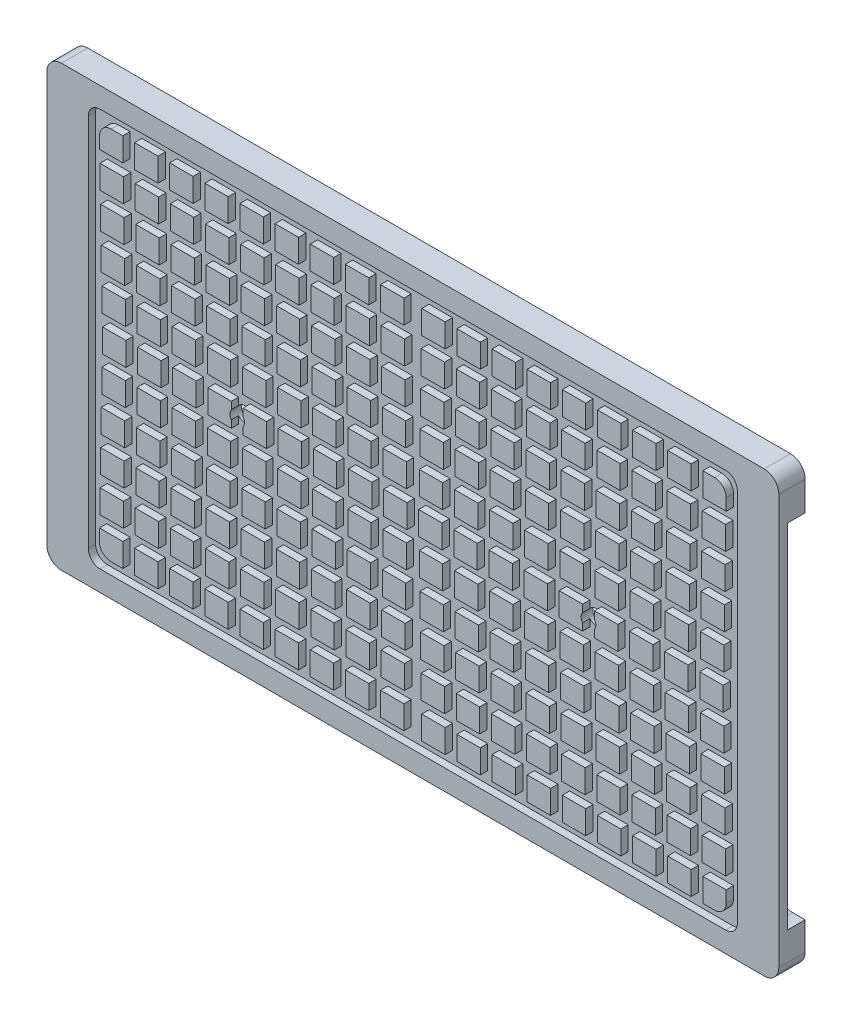
SolidWorks part; units mm, degrees
ref_plane "前视基准面" through (0, 0, 0) normal (0, 0, 1) x (1, 0, 0)
ref_plane "上视基准面" through (0, 0, 0) normal (0, 1, 0) x (1, 0, 0)
ref_plane "右视基准面" through (0, 0, 0) normal (1, 0, 0) x (0, 0, -1)
sketch "草图2" plane through (0, 0, 0) normal (0, 0, 1) x (1, 0, 0)
  line L1 (-120, 75) -> (120, 75)
  line L2 (-125, 70) -> (-125, -70)
  line L3 (-120, -75) -> (120, -75)
  line L4 (125, 70) -> (125, -70)
  line L5 (-125, 75) -> (125, -75) construction
  line L6 (-125, -75) -> (125, 75) construction
  arc A0 (125, 70) -> (120, 75) centre (120, 70) ccw
  arc A1 (125, -70) -> (120, -75) centre (120, -70) cw
  arc A2 (-120, -75) -> (-125, -70) centre (-120, -70) cw
  arc A3 (-125, 70) -> (-120, 75) centre (-120, 70) cw
  point P0 (0, 0)
  dimension "D3" = 5
  dimension "D1" = 250
  dimension "D2" = 150
extrude "凸台-拉伸1" add sketch "草图2" along normal blind 9
sketch "草图3" plane through (0, 0, 0) normal (0, 0, -1) x (-1, 0, 0)
  line L10 (-100, 65) -> (100, 65) construction
  line L11 (-99.2533, 65) -> (99.2533, 65)
  line L12 (-105, 59.2533) -> (-105, -59.2533)
  line L13 (-99.2533, -65) -> (99.2533, -65)
  line L14 (105, 59.2533) -> (105, -59.2533)
  line L15 (-105, 65) -> (105, -65) construction
  line L16 (-105, -65) -> (105, 65) construction
  line L17 (-105, -60) -> (-105, 60) construction
  line L18 (-99.2533, 67) -> (99.2533, 67)
  line L19 (107, 59.2533) -> (107, -59.2533)
  line L20 (-99.2533, -67) -> (99.2533, -67)
  line L21 (-107, 59.2533) -> (-107, -59.2533)
  line L22 (-106.0527, 63.2995) -> (103.9473, -66.7005) construction
  line L23 (-103.9473, -66.7005) -> (106.0527, 63.2995) construction
  arc A8 (105, 59.2533) -> (99.2533, 65) centre (99.2533, 59.2533) ccw
  arc A9 (105, -59.2533) -> (99.2533, -65) centre (99.2533, -59.2533) cw
  arc A10 (-105, -59.2533) -> (-99.2533, -65) centre (-99.2533, -59.2533) ccw
  arc A11 (-105, 59.2533) -> (-99.2533, 65) centre (-99.2533, 59.2533) cw
  arc A12 (107, 59.2533) -> (99.2533, 67) centre (99.2533, 59.2533) ccw
  arc A13 (107, -59.2533) -> (99.2533, -67) centre (99.2533, -59.2533) cw
  arc A14 (-107, -59.2533) -> (-99.2533, -67) centre (-99.2533, -59.2533) ccw
  arc A15 (-107, 59.2533) -> (-99.2533, 67) centre (-99.2533, 59.2533) cw
  point P0 (0, 0)
  dimension "D2" = 0
  dimension "D3" = 5.7467
  dimension "D1" = 0
  dimension "D4" = 2
extrude "凸台-拉伸2" add sketch "草图3" along normal blind 0.6
sketch "草图4" plane through (0, 0, 0) normal (0, 0, -1) x (-1, 0, 0)
  line L0 (125, 70) -> (125, -70) construction
  line L1 (125, -60.3809) -> (120.7467, -60.3809)
  line L2 (125, -60.3809) -> (125, 60)
  line L3 (125, 60) -> (120.7467, 60)
  line L4 (115, -54.6342) -> (115, 54.2533)
  line L5 (115, -55) -> (115, 55) construction
  line L6 (0, 0) -> (0, 16.1267) construction
  line L7 (-115, -54.6342) -> (-115, 54.2533)
  line L8 (-125, 60) -> (-120.7467, 60)
  line L9 (-125, -60.3809) -> (-125, 60)
  line L10 (-125, -60.3809) -> (-120.7467, -60.3809)
  arc A0 (115, -54.6342) -> (120.7467, -60.3809) centre (120.7467, -54.6342) ccw
  arc A1 (120.7467, 60) -> (115, 54.2533) centre (120.7467, 54.2533) ccw
  arc A2 (-120.7467, 60) -> (-115, 54.2533) centre (-120.7467, 54.2533) cw
  arc A3 (-115, -54.6342) -> (-120.7467, -60.3809) centre (-120.7467, -54.6342) cw
  dimension "D2" = 5.7467
  dimension "D1" = 0
extrude "切除-拉伸1" cut sketch "草图4" against normal blind 6 contours L7 A2 L8 L9 L10 A3 | L4 A1 L3 L2 L1 A0
sketch "草图5" plane through (0, -75, 0) normal (0, -1, 0) x (1, 0, 0)
  line L0 (0, 0) -> (0, 17.4603) construction
  line L1 (-120, 0) -> (120, 0) construction
  circle A0 centre (-15, 3.5) radius 2.25
  circle A1 centre (15, 3.5) radius 2.25
  dimension "D1" = 4.5
  dimension "D2" = 3.5
  dimension "D3" = 15
extrude "切除-拉伸2" cut sketch "草图5" against normal blind 15 contours A0 | A1
sketch "草图7" plane through (0, 0, 0) normal (0, 0, -1) x (-1, 0, 0)
  line L0 (0, 0) -> (-11.7747, 0) construction
  line L1 (0, 0) -> (0, -10.772) construction
  circle A0 centre (60, 0) radius 2.5
  circle A1 centre (-60, 0) radius 2.5
  dimension "D1" = 5
  dimension "D2" = 5
  dimension "D3" = 60
  dimension "D4" = 60
extrude "切除-拉伸3" cut sketch "草图7" against normal blind 15
sketch "草图8" plane through (0, 0, 0) normal (0, 0, -1) x (-1, 0, 0)
  line L0 (0, -0.8411) -> (0, -18.4077) construction
  line L22 (-99.2533, -65) -> (99.2533, -65) construction
  line L23 (-95, 60) -> (100, 60)
  line L24 (-100, 55) -> (-100, -55)
  line L25 (-95, -60) -> (95, -60)
  line L26 (100, 60) -> (100, -55)
  line L27 (-100, 60) -> (100, -60) construction
  line L28 (-100, -60) -> (100, 60) construction
  line L29 (105, -59.2533) -> (105, 59.2533) construction
  line L30 (99.2533, 65) -> (-99.2533, 65) construction
  line L31 (-105, 59.2533) -> (-105, -59.2533) construction
  arc A13 (100, -55) -> (95, -60) centre (95, -55) cw
  arc A14 (-100, -55) -> (-95, -60) centre (-95, -55) ccw
  arc A15 (-95, 60) -> (-100, 55) centre (-95, 55) ccw
  circle M1 centre (60, 0) radius 2.5
  circle M2 centre (-60, 0) radius 2.5
  dimension "D2" = 5
  dimension "D5" = 5
  dimension "D1" = 5
  dimension "D3" = 5
  dimension "D4" = 5
extrude "切除-拉伸4" cut sketch "草图8" against normal blind 5 contours M1 | M2 region at (-0.0222, 0.0132, 0)
sketch "草图9" plane through (0, 0, 9) normal (0, 0, 1) x (1, 0, 0)
  line L0 (0, 0) -> (0, 17.992) construction
  line L1 (0, 0) -> (-10.173, 0) construction
  line L2 (-14, -4) -> (-22, -4)
  line L3 (-2, -4) -> (-10, -4)
  line L4 (-2, -4) -> (-2, 4)
  line L5 (-2, 4) -> (-10, 4)
  line L6 (-10, -4) -> (-10, 4)
  line L7 (-2, -4) -> (-10, 4) construction
  line L8 (-2, 4) -> (-10, -4) construction
  line L9 (-14, -4) -> (-14, 4)
  line L10 (-14, 4) -> (-22, 4)
  line L11 (-22, -4) -> (-22, 4)
  line L12 (-14, -4) -> (-22, 4) construction
  line L13 (-14, 4) -> (-22, -4) construction
  line L14 (-26, -4) -> (-34, -4)
  line L15 (-26, -4) -> (-26, 4)
  line L16 (-26, 4) -> (-34, 4)
  line L17 (-34, -4) -> (-34, 4)
  line L18 (-26, -4) -> (-34, 4) construction
  line L19 (-26, 4) -> (-34, -4) construction
  line L20 (-38, -4) -> (-46, -4)
  line L21 (-38, -4) -> (-38, 4)
  line L22 (-38, 4) -> (-46, 4)
  line L23 (-46, -4) -> (-46, 4)
  line L24 (-38, -4) -> (-46, 4) construction
  line L25 (-38, 4) -> (-46, -4) construction
  line L26 (-50, -4) -> (-58, -4)
  line L27 (-50, -4) -> (-50, 4)
  line L28 (-50, 4) -> (-58, 4)
  line L29 (-58, -4) -> (-58, -1.5)
  line L30 (-50, -4) -> (-58, 4) construction
  line L31 (-50, 4) -> (-58, -4) construction
  line L32 (-62, -4) -> (-70, -4)
  line L33 (-62, -4) -> (-62, -1.5)
  line L34 (-62, 4) -> (-70, 4)
  line L35 (-70, -4) -> (-70, 4)
  line L36 (-62, -4) -> (-70, 4) construction
  line L37 (-62, 4) -> (-70, -4) construction
  line L38 (-74, -4) -> (-82, -4)
  line L39 (-74, -4) -> (-74, 4)
  line L40 (-74, 4) -> (-82, 4)
  line L41 (-82, -4) -> (-82, 4)
  line L42 (-74, -4) -> (-82, 4) construction
  line L43 (-74, 4) -> (-82, -4) construction
  line L44 (-86, -4) -> (-94, -4)
  line L45 (-86, -4) -> (-86, 4)
  line L46 (-86, 4) -> (-94, 4)
  line L47 (-94, -4) -> (-94, 4)
  line L48 (-86, -4) -> (-94, 4) construction
  line L49 (-86, 4) -> (-94, -4) construction
  line L50 (-98, -4) -> (-106, -4)
  line L51 (-98, -4) -> (-98, 4)
  line L52 (-98, 4) -> (-106, 4)
  line L53 (-106, -4) -> (-106, 4)
  line L54 (-98, -4) -> (-106, 4) construction
  line L55 (-98, 4) -> (-106, -4) construction
  line L56 (-14.2094, 7.9982) -> (-22.2094, 7.9982)
  line L57 (-14.2094, 7.9982) -> (-14.2094, 15.9982)
  line L58 (-14.2094, 15.9982) -> (-22.2094, 15.9982)
  line L59 (-22.2094, 7.9982) -> (-22.2094, 15.9982)
  line L60 (-14.2094, 7.9982) -> (-22.2094, 15.9982) construction
  line L61 (-14.2094, 15.9982) -> (-22.2094, 7.9982) construction
  line L62 (-26.2094, 7.9982) -> (-34.2094, 7.9982)
  line L63 (-26.2094, 7.9982) -> (-26.2094, 15.9982)
  line L64 (-26.2094, 15.9982) -> (-34.2094, 15.9982)
  line L65 (-34.2094, 7.9982) -> (-34.2094, 15.9982)
  line L66 (-26.2094, 7.9982) -> (-34.2094, 15.9982) construction
  line L67 (-26.2094, 15.9982) -> (-34.2094, 7.9982) construction
  line L68 (-38.2094, 7.9982) -> (-46.2094, 7.9982)
  line L69 (-38.2094, 7.9982) -> (-38.2094, 15.9982)
  line L70 (-38.2094, 15.9982) -> (-46.2094, 15.9982)
  line L71 (-46.2094, 7.9982) -> (-46.2094, 15.9982)
  line L72 (-38.2094, 7.9982) -> (-46.2094, 15.9982) construction
  line L73 (-38.2094, 15.9982) -> (-46.2094, 7.9982) construction
  line L74 (-50.2094, 7.9982) -> (-58.2094, 7.9982)
  line L75 (-50.2094, 7.9982) -> (-50.2094, 15.9982)
  line L76 (-50.2094, 15.9982) -> (-58.2094, 15.9982)
  line L77 (-58.2094, 7.9982) -> (-58.2094, 15.9982)
  line L78 (-50.2094, 7.9982) -> (-58.2094, 15.9982) construction
  line L79 (-50.2094, 15.9982) -> (-58.2094, 7.9982) construction
  line L80 (-62.2094, 7.9982) -> (-70.2094, 7.9982)
  line L81 (-62.2094, 7.9982) -> (-62.2094, 15.9982)
  line L82 (-62.2094, 15.9982) -> (-70.2094, 15.9982)
  line L83 (-70.2094, 7.9982) -> (-70.2094, 15.9982)
  line L84 (-62.2094, 7.9982) -> (-70.2094, 15.9982) construction
  line L85 (-62.2094, 15.9982) -> (-70.2094, 7.9982) construction
  line L86 (-74.2094, 7.9982) -> (-82.2094, 7.9982)
  line L87 (-74.2094, 7.9982) -> (-74.2094, 15.9982)
  line L88 (-74.2094, 15.9982) -> (-82.2094, 15.9982)
  line L89 (-82.2094, 7.9982) -> (-82.2094, 15.9982)
  line L90 (-74.2094, 7.9982) -> (-82.2094, 15.9982) construction
  line L91 (-74.2094, 15.9982) -> (-82.2094, 7.9982) construction
  line L92 (-86.2094, 7.9982) -> (-94.2094, 7.9982)
  line L93 (-86.2094, 7.9982) -> (-86.2094, 15.9982)
  line L94 (-86.2094, 15.9982) -> (-94.2094, 15.9982)
  line L95 (-94.2094, 7.9982) -> (-94.2094, 15.9982)
  line L96 (-86.2094, 7.9982) -> (-94.2094, 15.9982) construction
  line L97 (-86.2094, 15.9982) -> (-94.2094, 7.9982) construction
  line L98 (-98.2094, 7.9982) -> (-106.2094, 7.9982)
  line L99 (-98.2094, 7.9982) -> (-98.2094, 15.9982)
  line L100 (-98.2094, 15.9982) -> (-106.2094, 15.9982)
  line L101 (-106.2094, 7.9982) -> (-106.2094, 15.9982)
  line L102 (-98.2094, 7.9982) -> (-106.2094, 15.9982) construction
  line L103 (-98.2094, 15.9982) -> (-106.2094, 7.9982) construction
  line L104 (-14.4189, 19.9963) -> (-22.4189, 19.9963)
  line L105 (-14.4189, 19.9963) -> (-14.4189, 27.9963)
  line L106 (-14.4189, 27.9963) -> (-22.4189, 27.9963)
  line L107 (-22.4189, 19.9963) -> (-22.4189, 27.9963)
  line L108 (-14.4189, 19.9963) -> (-22.4189, 27.9963) construction
  line L109 (-14.4189, 27.9963) -> (-22.4189, 19.9963) construction
  line L110 (-26.4189, 19.9963) -> (-34.4189, 19.9963)
  line L111 (-26.4189, 19.9963) -> (-26.4189, 27.9963)
  line L112 (-26.4189, 27.9963) -> (-34.4189, 27.9963)
  line L113 (-34.4189, 19.9963) -> (-34.4189, 27.9963)
  line L114 (-26.4189, 19.9963) -> (-34.4189, 27.9963) construction
  line L115 (-26.4189, 27.9963) -> (-34.4189, 19.9963) construction
  line L116 (-38.4189, 19.9963) -> (-46.4189, 19.9963)
  line L117 (-38.4189, 19.9963) -> (-38.4189, 27.9963)
  line L118 (-38.4189, 27.9963) -> (-46.4189, 27.9963)
  line L119 (-46.4189, 19.9963) -> (-46.4189, 27.9963)
  line L120 (-38.4189, 19.9963) -> (-46.4189, 27.9963) construction
  line L121 (-38.4189, 27.9963) -> (-46.4189, 19.9963) construction
  line L122 (-50.4189, 19.9963) -> (-58.4189, 19.9963)
  line L123 (-50.4189, 19.9963) -> (-50.4189, 27.9963)
  line L124 (-50.4189, 27.9963) -> (-58.4189, 27.9963)
  line L125 (-58.4189, 19.9963) -> (-58.4189, 27.9963)
  line L126 (-50.4189, 19.9963) -> (-58.4189, 27.9963) construction
  line L127 (-50.4189, 27.9963) -> (-58.4189, 19.9963) construction
  line L128 (-62.4189, 19.9963) -> (-70.4189, 19.9963)
  line L129 (-62.4189, 19.9963) -> (-62.4189, 27.9963)
  line L130 (-62.4189, 27.9963) -> (-70.4189, 27.9963)
  line L131 (-70.4189, 19.9963) -> (-70.4189, 27.9963)
  line L132 (-62.4189, 19.9963) -> (-70.4189, 27.9963) construction
  line L133 (-62.4189, 27.9963) -> (-70.4189, 19.9963) construction
  line L134 (-74.4189, 19.9963) -> (-82.4189, 19.9963)
  line L135 (-74.4189, 19.9963) -> (-74.4189, 27.9963)
  line L136 (-74.4189, 27.9963) -> (-82.4189, 27.9963)
  line L137 (-82.4189, 19.9963) -> (-82.4189, 27.9963)
  line L138 (-74.4189, 19.9963) -> (-82.4189, 27.9963) construction
  line L139 (-74.4189, 27.9963) -> (-82.4189, 19.9963) construction
  line L140 (-86.4189, 19.9963) -> (-94.4189, 19.9963)
  line L141 (-86.4189, 19.9963) -> (-86.4189, 27.9963)
  line L142 (-86.4189, 27.9963) -> (-94.4189, 27.9963)
  line L143 (-94.4189, 19.9963) -> (-94.4189, 27.9963)
  line L144 (-86.4189, 19.9963) -> (-94.4189, 27.9963) construction
  line L145 (-86.4189, 27.9963) -> (-94.4189, 19.9963) construction
  line L146 (-98.4189, 19.9963) -> (-106.4189, 19.9963)
  line L147 (-98.4189, 19.9963) -> (-98.4189, 27.9963)
  line L148 (-98.4189, 27.9963) -> (-106.4189, 27.9963)
  line L149 (-106.4189, 19.9963) -> (-106.4189, 27.9963)
  line L150 (-98.4189, 19.9963) -> (-106.4189, 27.9963) construction
  line L151 (-98.4189, 27.9963) -> (-106.4189, 19.9963) construction
  line L152 (-14.6283, 31.9945) -> (-22.6283, 31.9945)
  line L153 (-14.6283, 31.9945) -> (-14.6283, 39.9945)
  line L154 (-14.6283, 39.9945) -> (-22.6283, 39.9945)
  line L155 (-22.6283, 31.9945) -> (-22.6283, 39.9945)
  line L156 (-14.6283, 31.9945) -> (-22.6283, 39.9945) construction
  line L157 (-14.6283, 39.9945) -> (-22.6283, 31.9945) construction
  line L158 (-26.6283, 31.9945) -> (-34.6283, 31.9945)
  line L159 (-26.6283, 31.9945) -> (-26.6283, 39.9945)
  line L160 (-26.6283, 39.9945) -> (-34.6283, 39.9945)
  line L161 (-34.6283, 31.9945) -> (-34.6283, 39.9945)
  line L162 (-26.6283, 31.9945) -> (-34.6283, 39.9945) construction
  line L163 (-26.6283, 39.9945) -> (-34.6283, 31.9945) construction
  line L164 (-38.6283, 31.9945) -> (-46.6283, 31.9945)
  line L165 (-38.6283, 31.9945) -> (-38.6283, 39.9945)
  line L166 (-38.6283, 39.9945) -> (-46.6283, 39.9945)
  line L167 (-46.6283, 31.9945) -> (-46.6283, 39.9945)
  line L168 (-38.6283, 31.9945) -> (-46.6283, 39.9945) construction
  line L169 (-38.6283, 39.9945) -> (-46.6283, 31.9945) construction
  line L170 (-50.6283, 31.9945) -> (-58.6283, 31.9945)
  line L171 (-50.6283, 31.9945) -> (-50.6283, 39.9945)
  line L172 (-50.6283, 39.9945) -> (-58.6283, 39.9945)
  line L173 (-58.6283, 31.9945) -> (-58.6283, 39.9945)
  line L174 (-50.6283, 31.9945) -> (-58.6283, 39.9945) construction
  line L175 (-50.6283, 39.9945) -> (-58.6283, 31.9945) construction
  line L176 (-62.6283, 31.9945) -> (-70.6283, 31.9945)
  line L177 (-62.6283, 31.9945) -> (-62.6283, 39.9945)
  line L178 (-62.6283, 39.9945) -> (-70.6283, 39.9945)
  line L179 (-70.6283, 31.9945) -> (-70.6283, 39.9945)
  line L180 (-62.6283, 31.9945) -> (-70.6283, 39.9945) construction
  line L181 (-62.6283, 39.9945) -> (-70.6283, 31.9945) construction
  line L182 (-74.6283, 31.9945) -> (-82.6283, 31.9945)
  line L183 (-74.6283, 31.9945) -> (-74.6283, 39.9945)
  line L184 (-74.6283, 39.9945) -> (-82.6283, 39.9945)
  line L185 (-82.6283, 31.9945) -> (-82.6283, 39.9945)
  line L186 (-74.6283, 31.9945) -> (-82.6283, 39.9945) construction
  line L187 (-74.6283, 39.9945) -> (-82.6283, 31.9945) construction
  line L188 (-86.6283, 31.9945) -> (-94.6283, 31.9945)
  line L189 (-86.6283, 31.9945) -> (-86.6283, 39.9945)
  line L190 (-86.6283, 39.9945) -> (-94.6283, 39.9945)
  line L191 (-94.6283, 31.9945) -> (-94.6283, 39.9945)
  line L192 (-86.6283, 31.9945) -> (-94.6283, 39.9945) construction
  line L193 (-86.6283, 39.9945) -> (-94.6283, 31.9945) construction
  line L194 (-98.6283, 31.9945) -> (-106.6283, 31.9945)
  line L195 (-98.6283, 31.9945) -> (-98.6283, 39.9945)
  line L196 (-98.6283, 39.9945) -> (-106.6283, 39.9945)
  line L197 (-106.6283, 31.9945) -> (-106.6283, 39.9945)
  line L198 (-98.6283, 31.9945) -> (-106.6283, 39.9945) construction
  line L199 (-98.6283, 39.9945) -> (-106.6283, 31.9945) construction
  line L200 (-14.8377, 43.9927) -> (-22.8377, 43.9927)
  line L201 (-14.8377, 43.9927) -> (-14.8377, 51.9927)
  line L202 (-14.8377, 51.9927) -> (-22.8377, 51.9927)
  line L203 (-22.8377, 43.9927) -> (-22.8377, 51.9927)
  line L204 (-14.8377, 43.9927) -> (-22.8377, 51.9927) construction
  line L205 (-14.8377, 51.9927) -> (-22.8377, 43.9927) construction
  line L206 (-26.8377, 43.9927) -> (-34.8377, 43.9927)
  line L207 (-26.8377, 43.9927) -> (-26.8377, 51.9927)
  line L208 (-26.8377, 51.9927) -> (-34.8377, 51.9927)
  line L209 (-34.8377, 43.9927) -> (-34.8377, 51.9927)
  line L210 (-26.8377, 43.9927) -> (-34.8377, 51.9927) construction
  line L211 (-26.8377, 51.9927) -> (-34.8377, 43.9927) construction
  line L212 (-38.8377, 43.9927) -> (-46.8377, 43.9927)
  line L213 (-38.8377, 43.9927) -> (-38.8377, 51.9927)
  line L214 (-38.8377, 51.9927) -> (-46.8377, 51.9927)
  line L215 (-46.8377, 43.9927) -> (-46.8377, 51.9927)
  line L216 (-38.8377, 43.9927) -> (-46.8377, 51.9927) construction
  line L217 (-38.8377, 51.9927) -> (-46.8377, 43.9927) construction
  line L218 (-50.8377, 43.9927) -> (-58.8377, 43.9927)
  line L219 (-50.8377, 43.9927) -> (-50.8377, 51.9927)
  line L220 (-50.8377, 51.9927) -> (-58.8377, 51.9927)
  line L221 (-58.8377, 43.9927) -> (-58.8377, 51.9927)
  line L222 (-50.8377, 43.9927) -> (-58.8377, 51.9927) construction
  line L223 (-50.8377, 51.9927) -> (-58.8377, 43.9927) construction
  line L224 (-62.8377, 43.9927) -> (-70.8377, 43.9927)
  line L225 (-62.8377, 43.9927) -> (-62.8377, 51.9927)
  line L226 (-62.8377, 51.9927) -> (-70.8377, 51.9927)
  line L227 (-70.8377, 43.9927) -> (-70.8377, 51.9927)
  line L228 (-62.8377, 43.9927) -> (-70.8377, 51.9927) construction
  line L229 (-62.8377, 51.9927) -> (-70.8377, 43.9927) construction
  line L230 (-74.8377, 43.9927) -> (-82.8377, 43.9927)
  line L231 (-74.8377, 43.9927) -> (-74.8377, 51.9927)
  line L232 (-74.8377, 51.9927) -> (-82.8377, 51.9927)
  line L233 (-82.8377, 43.9927) -> (-82.8377, 51.9927)
  line L234 (-74.8377, 43.9927) -> (-82.8377, 51.9927) construction
  line L235 (-74.8377, 51.9927) -> (-82.8377, 43.9927) construction
  line L236 (-86.8377, 43.9927) -> (-94.8377, 43.9927)
  line L237 (-86.8377, 43.9927) -> (-86.8377, 51.9927)
  line L238 (-86.8377, 51.9927) -> (-94.8377, 51.9927)
  line L239 (-94.8377, 43.9927) -> (-94.8377, 51.9927)
  line L240 (-86.8377, 43.9927) -> (-94.8377, 51.9927) construction
  line L241 (-86.8377, 51.9927) -> (-94.8377, 43.9927) construction
  line L242 (-98.8377, 43.9927) -> (-106.8377, 43.9927)
  line L243 (-98.8377, 43.9927) -> (-98.8377, 51.9927)
  line L244 (-98.8377, 51.9927) -> (-106.8377, 51.9927)
  line L245 (-106.8377, 43.9927) -> (-106.8377, 51.9927)
  line L246 (-98.8377, 43.9927) -> (-106.8377, 51.9927) construction
  line L247 (-98.8377, 51.9927) -> (-106.8377, 43.9927) construction
  line L248 (-15.0471, 55.9909) -> (-23.0471, 55.9909)
  line L249 (-15.0471, 55.9909) -> (-15.0471, 63.9909)
  line L250 (-15.0471, 63.9909) -> (-23.0471, 63.9909)
  line L251 (-23.0471, 55.9909) -> (-23.0471, 63.9909)
  line L252 (-15.0471, 55.9909) -> (-23.0471, 63.9909) construction
  line L253 (-15.0471, 63.9909) -> (-23.0471, 55.9909) construction
  line L254 (-27.0471, 55.9909) -> (-35.0471, 55.9909)
  line L255 (-27.0471, 55.9909) -> (-27.0471, 63.9909)
  line L256 (-27.0471, 63.9909) -> (-35.0471, 63.9909)
  line L257 (-35.0471, 55.9909) -> (-35.0471, 63.9909)
  line L258 (-27.0471, 55.9909) -> (-35.0471, 63.9909) construction
  line L259 (-27.0471, 63.9909) -> (-35.0471, 55.9909) construction
  line L260 (-39.0471, 55.9909) -> (-47.0471, 55.9909)
  line L261 (-39.0471, 55.9909) -> (-39.0471, 63.9909)
  line L262 (-39.0471, 63.9909) -> (-47.0471, 63.9909)
  line L263 (-47.0471, 55.9909) -> (-47.0471, 63.9909)
  line L264 (-39.0471, 55.9909) -> (-47.0471, 63.9909) construction
  line L265 (-39.0471, 63.9909) -> (-47.0471, 55.9909) construction
  line L266 (-51.0471, 55.9909) -> (-59.0471, 55.9909)
  line L267 (-51.0471, 55.9909) -> (-51.0471, 63.9909)
  line L268 (-51.0471, 63.9909) -> (-59.0471, 63.9909)
  line L269 (-59.0471, 55.9909) -> (-59.0471, 63.9909)
  line L270 (-51.0471, 55.9909) -> (-59.0471, 63.9909) construction
  line L271 (-51.0471, 63.9909) -> (-59.0471, 55.9909) construction
  line L272 (-63.0471, 55.9909) -> (-71.0471, 55.9909)
  line L273 (-63.0471, 55.9909) -> (-63.0471, 63.9909)
  line L274 (-63.0471, 63.9909) -> (-71.0471, 63.9909)
  line L275 (-71.0471, 55.9909) -> (-71.0471, 63.9909)
  line L276 (-63.0471, 55.9909) -> (-71.0471, 63.9909) construction
  line L277 (-63.0471, 63.9909) -> (-71.0471, 55.9909) construction
  line L278 (-75.0471, 55.9909) -> (-83.0471, 55.9909)
  line L279 (-75.0471, 55.9909) -> (-75.0471, 63.9909)
  line L280 (-75.0471, 63.9909) -> (-83.0471, 63.9909)
  line L281 (-83.0471, 55.9909) -> (-83.0471, 63.9909)
  line L282 (-75.0471, 55.9909) -> (-83.0471, 63.9909) construction
  line L283 (-75.0471, 63.9909) -> (-83.0471, 55.9909) construction
  line L284 (-87.0471, 55.9909) -> (-95.0471, 55.9909)
  line L285 (-87.0471, 55.9909) -> (-87.0471, 63.9909)
  line L286 (-87.0471, 63.9909) -> (-95.0471, 63.9909)
  line L287 (-95.0471, 55.9909) -> (-95.0471, 63.9909)
  line L288 (-87.0471, 55.9909) -> (-95.0471, 63.9909) construction
  line L289 (-87.0471, 63.9909) -> (-95.0471, 55.9909) construction
  line L290 (-99.0471, 55.9909) -> (-107.0471, 55.9909)
  line L291 (-99.0471, 55.9909) -> (-99.0471, 63.9909)
  line L292 (-99.0471, 63.9909) -> (-103.0471, 63.9909)
  line L293 (-107.0471, 55.9909) -> (-107.0471, 59.9909)
  line L294 (-99.0471, 55.9909) -> (-107.0471, 63.9909) construction
  line L295 (-99.0471, 63.9909) -> (-107.0471, 55.9909) construction
  line L296 (-2.2094, 7.9982) -> (-10.2094, 7.9982)
  line L297 (-2.2094, 7.9982) -> (-2.2094, 15.9982)
  line L298 (-2.2094, 15.9982) -> (-10.2094, 15.9982)
  line L299 (-10.2094, 7.9982) -> (-10.2094, 15.9982)
  line L300 (-2.2094, 7.9982) -> (-10.2094, 15.9982) construction
  line L301 (-2.2094, 15.9982) -> (-10.2094, 7.9982) construction
  line L302 (-2.4189, 19.9963) -> (-10.4189, 19.9963)
  line L303 (-2.4189, 19.9963) -> (-2.4189, 27.9963)
  line L304 (-2.4189, 27.9963) -> (-10.4189, 27.9963)
  line L305 (-10.4189, 19.9963) -> (-10.4189, 27.9963)
  line L306 (-2.4189, 19.9963) -> (-10.4189, 27.9963) construction
  line L307 (-2.4189, 27.9963) -> (-10.4189, 19.9963) construction
  line L308 (-2.6283, 31.9945) -> (-10.6283, 31.9945)
  line L309 (-2.6283, 31.9945) -> (-2.6283, 39.9945)
  line L310 (-2.6283, 39.9945) -> (-10.6283, 39.9945)
  line L311 (-10.6283, 31.9945) -> (-10.6283, 39.9945)
  line L312 (-2.6283, 31.9945) -> (-10.6283, 39.9945) construction
  line L313 (-2.6283, 39.9945) -> (-10.6283, 31.9945) construction
  line L314 (-2.8377, 43.9927) -> (-10.8377, 43.9927)
  line L315 (-2.8377, 43.9927) -> (-2.8377, 51.9927)
  line L316 (-2.8377, 51.9927) -> (-10.8377, 51.9927)
  line L317 (-10.8377, 43.9927) -> (-10.8377, 51.9927)
  line L318 (-2.8377, 43.9927) -> (-10.8377, 51.9927) construction
  line L319 (-2.8377, 51.9927) -> (-10.8377, 43.9927) construction
  line L320 (-3.0471, 55.9909) -> (-11.0471, 55.9909)
  line L321 (-3.0471, 55.9909) -> (-3.0471, 63.9909)
  line L322 (-3.0471, 63.9909) -> (-11.0471, 63.9909)
  line L323 (-11.0471, 55.9909) -> (-11.0471, 63.9909)
  line L324 (-3.0471, 55.9909) -> (-11.0471, 63.9909) construction
  line L325 (-3.0471, 63.9909) -> (-11.0471, 55.9909) construction
  line L326 (-6, 0) -> (-18, 0) construction
  line L327 (-6, 0) -> (-6.2094, 11.9982) construction
  line L328 (6, 0) -> (6.2094, 11.9982) construction
  line L329 (6, 0) -> (18, 0) construction
  line L330 (3.0471, 63.9909) -> (11.0471, 55.9909) construction
  line L331 (3.0471, 55.9909) -> (11.0471, 63.9909) construction
  line L332 (2.8377, 51.9927) -> (10.8377, 43.9927) construction
  line L333 (2.8377, 43.9927) -> (10.8377, 51.9927) construction
  line L334 (2.6283, 39.9945) -> (10.6283, 31.9945) construction
  line L335 (2.6283, 31.9945) -> (10.6283, 39.9945) construction
  line L336 (2.4189, 27.9963) -> (10.4189, 19.9963) construction
  line L337 (2.4189, 19.9963) -> (10.4189, 27.9963) construction
  line L338 (2.2094, 15.9982) -> (10.2094, 7.9982) construction
  line L339 (2.2094, 7.9982) -> (10.2094, 15.9982) construction
  line L340 (99.0471, 63.9909) -> (107.0471, 55.9909) construction
  line L341 (99.0471, 55.9909) -> (107.0471, 63.9909) construction
  line L342 (87.0471, 63.9909) -> (95.0471, 55.9909) construction
  line L343 (87.0471, 55.9909) -> (95.0471, 63.9909) construction
  line L344 (75.0471, 63.9909) -> (83.0471, 55.9909) construction
  line L345 (75.0471, 55.9909) -> (83.0471, 63.9909) construction
  line L346 (63.0471, 63.9909) -> (71.0471, 55.9909) construction
  line L347 (63.0471, 55.9909) -> (71.0471, 63.9909) construction
  line L348 (51.0471, 63.9909) -> (59.0471, 55.9909) construction
  line L349 (51.0471, 55.9909) -> (59.0471, 63.9909) construction
  line L350 (39.0471, 63.9909) -> (47.0471, 55.9909) construction
  line L351 (39.0471, 55.9909) -> (47.0471, 63.9909) construction
  line L352 (27.0471, 63.9909) -> (35.0471, 55.9909) construction
  line L353 (27.0471, 55.9909) -> (35.0471, 63.9909) construction
  line L354 (15.0471, 63.9909) -> (23.0471, 55.9909) construction
  line L355 (15.0471, 55.9909) -> (23.0471, 63.9909) construction
  line L356 (98.8377, 51.9927) -> (106.8377, 43.9927) construction
  line L357 (98.8377, 43.9927) -> (106.8377, 51.9927) construction
  line L358 (86.8377, 51.9927) -> (94.8377, 43.9927) construction
  line L359 (86.8377, 43.9927) -> (94.8377, 51.9927) construction
  line L360 (74.8377, 51.9927) -> (82.8377, 43.9927) construction
  line L361 (74.8377, 43.9927) -> (82.8377, 51.9927) construction
  line L362 (62.8377, 51.9927) -> (70.8377, 43.9927) construction
  line L363 (62.8377, 43.9927) -> (70.8377, 51.9927) construction
  line L364 (50.8377, 51.9927) -> (58.8377, 43.9927) construction
  line L365 (50.8377, 43.9927) -> (58.8377, 51.9927) construction
  line L366 (38.8377, 51.9927) -> (46.8377, 43.9927) construction
  line L367 (38.8377, 43.9927) -> (46.8377, 51.9927) construction
  line L368 (26.8377, 51.9927) -> (34.8377, 43.9927) construction
  line L369 (26.8377, 43.9927) -> (34.8377, 51.9927) construction
  line L370 (14.8377, 51.9927) -> (22.8377, 43.9927) construction
  line L371 (14.8377, 43.9927) -> (22.8377, 51.9927) construction
  line L372 (98.6283, 39.9945) -> (106.6283, 31.9945) construction
  line L373 (98.6283, 31.9945) -> (106.6283, 39.9945) construction
  line L374 (86.6283, 39.9945) -> (94.6283, 31.9945) construction
  line L375 (86.6283, 31.9945) -> (94.6283, 39.9945) construction
  line L376 (74.6283, 39.9945) -> (82.6283, 31.9945) construction
  line L377 (74.6283, 31.9945) -> (82.6283, 39.9945) construction
  line L378 (62.6283, 39.9945) -> (70.6283, 31.9945) construction
  line L379 (62.6283, 31.9945) -> (70.6283, 39.9945) construction
  line L380 (50.6283, 39.9945) -> (58.6283, 31.9945) construction
  line L381 (50.6283, 31.9945) -> (58.6283, 39.9945) construction
  line L382 (38.6283, 39.9945) -> (46.6283, 31.9945) construction
  line L383 (38.6283, 31.9945) -> (46.6283, 39.9945) construction
  line L384 (26.6283, 39.9945) -> (34.6283, 31.9945) construction
  line L385 (26.6283, 31.9945) -> (34.6283, 39.9945) construction
  line L386 (14.6283, 39.9945) -> (22.6283, 31.9945) construction
  line L387 (14.6283, 31.9945) -> (22.6283, 39.9945) construction
  line L388 (98.4189, 27.9963) -> (106.4189, 19.9963) construction
  line L389 (98.4189, 19.9963) -> (106.4189, 27.9963) construction
  line L390 (86.4189, 27.9963) -> (94.4189, 19.9963) construction
  line L391 (86.4189, 19.9963) -> (94.4189, 27.9963) construction
  line L392 (74.4189, 27.9963) -> (82.4189, 19.9963) construction
  line L393 (74.4189, 19.9963) -> (82.4189, 27.9963) construction
  line L394 (62.4189, 27.9963) -> (70.4189, 19.9963) construction
  line L395 (62.4189, 19.9963) -> (70.4189, 27.9963) construction
  line L396 (50.4189, 27.9963) -> (58.4189, 19.9963) construction
  line L397 (50.4189, 19.9963) -> (58.4189, 27.9963) construction
  line L398 (38.4189, 27.9963) -> (46.4189, 19.9963) construction
  line L399 (38.4189, 19.9963) -> (46.4189, 27.9963) construction
  line L400 (26.4189, 27.9963) -> (34.4189, 19.9963) construction
  line L401 (26.4189, 19.9963) -> (34.4189, 27.9963) construction
  line L402 (14.4189, 27.9963) -> (22.4189, 19.9963) construction
  line L403 (14.4189, 19.9963) -> (22.4189, 27.9963) construction
  line L404 (98.2094, 15.9982) -> (106.2094, 7.9982) construction
  line L405 (98.2094, 7.9982) -> (106.2094, 15.9982) construction
  line L406 (86.2094, 15.9982) -> (94.2094, 7.9982) construction
  line L407 (86.2094, 7.9982) -> (94.2094, 15.9982) construction
  line L408 (74.2094, 15.9982) -> (82.2094, 7.9982) construction
  line L409 (74.2094, 7.9982) -> (82.2094, 15.9982) construction
  line L410 (62.2094, 15.9982) -> (70.2094, 7.9982) construction
  line L411 (62.2094, 7.9982) -> (70.2094, 15.9982) construction
  line L412 (50.2094, 15.9982) -> (58.2094, 7.9982) construction
  line L413 (50.2094, 7.9982) -> (58.2094, 15.9982) construction
  line L414 (38.2094, 15.9982) -> (46.2094, 7.9982) construction
  line L415 (38.2094, 7.9982) -> (46.2094, 15.9982) construction
  line L416 (26.2094, 15.9982) -> (34.2094, 7.9982) construction
  line L417 (26.2094, 7.9982) -> (34.2094, 15.9982) construction
  line L418 (14.2094, 15.9982) -> (22.2094, 7.9982) construction
  line L419 (14.2094, 7.9982) -> (22.2094, 15.9982) construction
  line L420 (98, 4) -> (106, -4) construction
  line L421 (98, -4) -> (106, 4) construction
  line L422 (86, 4) -> (94, -4) construction
  line L423 (86, -4) -> (94, 4) construction
  line L424 (74, 4) -> (82, -4) construction
  line L425 (74, -4) -> (82, 4) construction
  line L426 (62, 4) -> (70, -4) construction
  line L427 (62, -4) -> (70, 4) construction
  line L428 (50, 4) -> (58, -4) construction
  line L429 (50, -4) -> (58, 4) construction
  line L430 (38, 4) -> (46, -4) construction
  line L431 (38, -4) -> (46, 4) construction
  line L432 (26, 4) -> (34, -4) construction
  line L433 (26, -4) -> (34, 4) construction
  line L434 (14, 4) -> (22, -4) construction
  line L435 (14, -4) -> (22, 4) construction
  line L436 (2, 4) -> (10, -4) construction
  line L437 (2, -4) -> (10, 4) construction
  line L438 (11.0471, 55.9909) -> (11.0471, 63.9909)
  line L439 (3.0471, 63.9909) -> (11.0471, 63.9909)
  line L440 (3.0471, 55.9909) -> (3.0471, 63.9909)
  line L441 (3.0471, 55.9909) -> (11.0471, 55.9909)
  line L442 (10.8377, 43.9927) -> (10.8377, 51.9927)
  line L443 (2.8377, 51.9927) -> (10.8377, 51.9927)
  line L444 (2.8377, 43.9927) -> (2.8377, 51.9927)
  line L445 (2.8377, 43.9927) -> (10.8377, 43.9927)
  line L446 (10.6283, 31.9945) -> (10.6283, 39.9945)
  line L447 (2.6283, 39.9945) -> (10.6283, 39.9945)
  line L448 (2.6283, 31.9945) -> (2.6283, 39.9945)
  line L449 (2.6283, 31.9945) -> (10.6283, 31.9945)
  line L450 (10.4189, 19.9963) -> (10.4189, 27.9963)
  line L451 (2.4189, 27.9963) -> (10.4189, 27.9963)
  line L452 (2.4189, 19.9963) -> (2.4189, 27.9963)
  line L453 (2.4189, 19.9963) -> (10.4189, 19.9963)
  line L454 (10.2094, 7.9982) -> (10.2094, 15.9982)
  line L455 (2.2094, 15.9982) -> (10.2094, 15.9982)
  line L456 (2.2094, 7.9982) -> (2.2094, 15.9982)
  line L457 (2.2094, 7.9982) -> (10.2094, 7.9982)
  line L458 (107.0471, 55.9909) -> (107.0471, 59.9909)
  line L459 (99.0471, 63.9909) -> (103.0471, 63.9909)
  line L460 (99.0471, 55.9909) -> (99.0471, 63.9909)
  line L461 (99.0471, 55.9909) -> (107.0471, 55.9909)
  line L462 (95.0471, 55.9909) -> (95.0471, 63.9909)
  line L463 (87.0471, 63.9909) -> (95.0471, 63.9909)
  line L464 (87.0471, 55.9909) -> (87.0471, 63.9909)
  line L465 (87.0471, 55.9909) -> (95.0471, 55.9909)
  line L466 (83.0471, 55.9909) -> (83.0471, 63.9909)
  line L467 (75.0471, 63.9909) -> (83.0471, 63.9909)
  line L468 (75.0471, 55.9909) -> (75.0471, 63.9909)
  line L469 (75.0471, 55.9909) -> (83.0471, 55.9909)
  line L470 (71.0471, 55.9909) -> (71.0471, 63.9909)
  line L471 (63.0471, 63.9909) -> (71.0471, 63.9909)
  line L472 (63.0471, 55.9909) -> (63.0471, 63.9909)
  line L473 (63.0471, 55.9909) -> (71.0471, 55.9909)
  line L474 (59.0471, 55.9909) -> (59.0471, 63.9909)
  line L475 (51.0471, 63.9909) -> (59.0471, 63.9909)
  line L476 (51.0471, 55.9909) -> (51.0471, 63.9909)
  line L477 (51.0471, 55.9909) -> (59.0471, 55.9909)
  line L478 (47.0471, 55.9909) -> (47.0471, 63.9909)
  line L479 (39.0471, 63.9909) -> (47.0471, 63.9909)
  line L480 (39.0471, 55.9909) -> (39.0471, 63.9909)
  line L481 (39.0471, 55.9909) -> (47.0471, 55.9909)
  line L482 (35.0471, 55.9909) -> (35.0471, 63.9909)
  line L483 (27.0471, 63.9909) -> (35.0471, 63.9909)
  line L484 (27.0471, 55.9909) -> (27.0471, 63.9909)
  line L485 (27.0471, 55.9909) -> (35.0471, 55.9909)
  line L486 (23.0471, 55.9909) -> (23.0471, 63.9909)
  line L487 (15.0471, 63.9909) -> (23.0471, 63.9909)
  line L488 (15.0471, 55.9909) -> (15.0471, 63.9909)
  line L489 (15.0471, 55.9909) -> (23.0471, 55.9909)
  line L490 (106.8377, 43.9927) -> (106.8377, 51.9927)
  line L491 (98.8377, 51.9927) -> (106.8377, 51.9927)
  line L492 (98.8377, 43.9927) -> (98.8377, 51.9927)
  line L493 (98.8377, 43.9927) -> (106.8377, 43.9927)
  line L494 (94.8377, 43.9927) -> (94.8377, 51.9927)
  line L495 (86.8377, 51.9927) -> (94.8377, 51.9927)
  line L496 (86.8377, 43.9927) -> (86.8377, 51.9927)
  line L497 (86.8377, 43.9927) -> (94.8377, 43.9927)
  line L498 (82.8377, 43.9927) -> (82.8377, 51.9927)
  line L499 (74.8377, 51.9927) -> (82.8377, 51.9927)
  line L500 (74.8377, 43.9927) -> (74.8377, 51.9927)
  line L501 (74.8377, 43.9927) -> (82.8377, 43.9927)
  line L502 (70.8377, 43.9927) -> (70.8377, 51.9927)
  line L503 (62.8377, 51.9927) -> (70.8377, 51.9927)
  line L504 (62.8377, 43.9927) -> (62.8377, 51.9927)
  line L505 (62.8377, 43.9927) -> (70.8377, 43.9927)
  line L506 (58.8377, 43.9927) -> (58.8377, 51.9927)
  line L507 (50.8377, 51.9927) -> (58.8377, 51.9927)
  line L508 (50.8377, 43.9927) -> (50.8377, 51.9927)
  line L509 (50.8377, 43.9927) -> (58.8377, 43.9927)
  line L510 (46.8377, 43.9927) -> (46.8377, 51.9927)
  line L511 (38.8377, 51.9927) -> (46.8377, 51.9927)
  line L512 (38.8377, 43.9927) -> (38.8377, 51.9927)
  line L513 (38.8377, 43.9927) -> (46.8377, 43.9927)
  line L514 (34.8377, 43.9927) -> (34.8377, 51.9927)
  line L515 (26.8377, 51.9927) -> (34.8377, 51.9927)
  line L516 (26.8377, 43.9927) -> (26.8377, 51.9927)
  line L517 (26.8377, 43.9927) -> (34.8377, 43.9927)
  line L518 (22.8377, 43.9927) -> (22.8377, 51.9927)
  line L519 (14.8377, 51.9927) -> (22.8377, 51.9927)
  line L520 (14.8377, 43.9927) -> (14.8377, 51.9927)
  line L521 (14.8377, 43.9927) -> (22.8377, 43.9927)
  line L522 (106.6283, 31.9945) -> (106.6283, 39.9945)
  line L523 (98.6283, 39.9945) -> (106.6283, 39.9945)
  line L524 (98.6283, 31.9945) -> (98.6283, 39.9945)
  line L525 (98.6283, 31.9945) -> (106.6283, 31.9945)
  line L526 (94.6283, 31.9945) -> (94.6283, 39.9945)
  line L527 (86.6283, 39.9945) -> (94.6283, 39.9945)
  line L528 (86.6283, 31.9945) -> (86.6283, 39.9945)
  line L529 (86.6283, 31.9945) -> (94.6283, 31.9945)
  line L530 (82.6283, 31.9945) -> (82.6283, 39.9945)
  line L531 (74.6283, 39.9945) -> (82.6283, 39.9945)
  line L532 (74.6283, 31.9945) -> (74.6283, 39.9945)
  line L533 (74.6283, 31.9945) -> (82.6283, 31.9945)
  line L534 (70.6283, 31.9945) -> (70.6283, 39.9945)
  line L535 (62.6283, 39.9945) -> (70.6283, 39.9945)
  line L536 (62.6283, 31.9945) -> (62.6283, 39.9945)
  line L537 (62.6283, 31.9945) -> (70.6283, 31.9945)
  line L538 (58.6283, 31.9945) -> (58.6283, 39.9945)
  line L539 (50.6283, 39.9945) -> (58.6283, 39.9945)
  line L540 (50.6283, 31.9945) -> (50.6283, 39.9945)
  line L541 (50.6283, 31.9945) -> (58.6283, 31.9945)
  line L542 (46.6283, 31.9945) -> (46.6283, 39.9945)
  line L543 (38.6283, 39.9945) -> (46.6283, 39.9945)
  line L544 (38.6283, 31.9945) -> (38.6283, 39.9945)
  line L545 (38.6283, 31.9945) -> (46.6283, 31.9945)
  line L546 (34.6283, 31.9945) -> (34.6283, 39.9945)
  line L547 (26.6283, 39.9945) -> (34.6283, 39.9945)
  line L548 (26.6283, 31.9945) -> (26.6283, 39.9945)
  line L549 (26.6283, 31.9945) -> (34.6283, 31.9945)
  line L550 (22.6283, 31.9945) -> (22.6283, 39.9945)
  line L551 (14.6283, 39.9945) -> (22.6283, 39.9945)
  line L552 (14.6283, 31.9945) -> (14.6283, 39.9945)
  line L553 (14.6283, 31.9945) -> (22.6283, 31.9945)
  line L554 (106.4189, 19.9963) -> (106.4189, 27.9963)
  line L555 (98.4189, 27.9963) -> (106.4189, 27.9963)
  line L556 (98.4189, 19.9963) -> (98.4189, 27.9963)
  line L557 (98.4189, 19.9963) -> (106.4189, 19.9963)
  line L558 (94.4189, 19.9963) -> (94.4189, 27.9963)
  line L559 (86.4189, 27.9963) -> (94.4189, 27.9963)
  line L560 (86.4189, 19.9963) -> (86.4189, 27.9963)
  line L561 (86.4189, 19.9963) -> (94.4189, 19.9963)
  line L562 (82.4189, 19.9963) -> (82.4189, 27.9963)
  line L563 (74.4189, 27.9963) -> (82.4189, 27.9963)
  line L564 (74.4189, 19.9963) -> (74.4189, 27.9963)
  line L565 (74.4189, 19.9963) -> (82.4189, 19.9963)
  line L566 (70.4189, 19.9963) -> (70.4189, 27.9963)
  line L567 (62.4189, 27.9963) -> (70.4189, 27.9963)
  line L568 (62.4189, 19.9963) -> (62.4189, 27.9963)
  line L569 (62.4189, 19.9963) -> (70.4189, 19.9963)
  line L570 (58.4189, 19.9963) -> (58.4189, 27.9963)
  line L571 (50.4189, 27.9963) -> (58.4189, 27.9963)
  line L572 (50.4189, 19.9963) -> (50.4189, 27.9963)
  line L573 (50.4189, 19.9963) -> (58.4189, 19.9963)
  line L574 (46.4189, 19.9963) -> (46.4189, 27.9963)
  line L575 (38.4189, 27.9963) -> (46.4189, 27.9963)
  line L576 (38.4189, 19.9963) -> (38.4189, 27.9963)
  line L577 (38.4189, 19.9963) -> (46.4189, 19.9963)
  line L578 (34.4189, 19.9963) -> (34.4189, 27.9963)
  line L579 (26.4189, 27.9963) -> (34.4189, 27.9963)
  line L580 (26.4189, 19.9963) -> (26.4189, 27.9963)
  line L581 (26.4189, 19.9963) -> (34.4189, 19.9963)
  line L582 (22.4189, 19.9963) -> (22.4189, 27.9963)
  line L583 (14.4189, 27.9963) -> (22.4189, 27.9963)
  line L584 (14.4189, 19.9963) -> (14.4189, 27.9963)
  line L585 (14.4189, 19.9963) -> (22.4189, 19.9963)
  line L586 (106.2094, 7.9982) -> (106.2094, 15.9982)
  line L587 (98.2094, 15.9982) -> (106.2094, 15.9982)
  line L588 (98.2094, 7.9982) -> (98.2094, 15.9982)
  line L589 (98.2094, 7.9982) -> (106.2094, 7.9982)
  line L590 (94.2094, 7.9982) -> (94.2094, 15.9982)
  line L591 (86.2094, 15.9982) -> (94.2094, 15.9982)
  line L592 (86.2094, 7.9982) -> (86.2094, 15.9982)
  line L593 (86.2094, 7.9982) -> (94.2094, 7.9982)
  line L594 (82.2094, 7.9982) -> (82.2094, 15.9982)
  line L595 (74.2094, 15.9982) -> (82.2094, 15.9982)
  line L596 (74.2094, 7.9982) -> (74.2094, 15.9982)
  line L597 (74.2094, 7.9982) -> (82.2094, 7.9982)
  line L598 (70.2094, 7.9982) -> (70.2094, 15.9982)
  line L599 (62.2094, 15.9982) -> (70.2094, 15.9982)
  line L600 (62.2094, 7.9982) -> (62.2094, 15.9982)
  line L601 (62.2094, 7.9982) -> (70.2094, 7.9982)
  line L602 (58.2094, 7.9982) -> (58.2094, 15.9982)
  line L603 (50.2094, 15.9982) -> (58.2094, 15.9982)
  line L604 (50.2094, 7.9982) -> (50.2094, 15.9982)
  line L605 (50.2094, 7.9982) -> (58.2094, 7.9982)
  line L606 (46.2094, 7.9982) -> (46.2094, 15.9982)
  line L607 (38.2094, 15.9982) -> (46.2094, 15.9982)
  line L608 (38.2094, 7.9982) -> (38.2094, 15.9982)
  line L609 (38.2094, 7.9982) -> (46.2094, 7.9982)
  line L610 (34.2094, 7.9982) -> (34.2094, 15.9982)
  line L611 (26.2094, 15.9982) -> (34.2094, 15.9982)
  line L612 (26.2094, 7.9982) -> (26.2094, 15.9982)
  line L613 (26.2094, 7.9982) -> (34.2094, 7.9982)
  line L614 (22.2094, 7.9982) -> (22.2094, 15.9982)
  line L615 (14.2094, 15.9982) -> (22.2094, 15.9982)
  line L616 (14.2094, 7.9982) -> (14.2094, 15.9982)
  line L617 (14.2094, 7.9982) -> (22.2094, 7.9982)
  line L618 (106, -4) -> (106, 4)
  line L619 (98, 4) -> (106, 4)
  line L620 (98, -4) -> (98, 4)
  line L621 (98, -4) -> (106, -4)
  line L622 (94, -4) -> (94, 4)
  line L623 (86, 4) -> (94, 4)
  line L624 (86, -4) -> (86, 4)
  line L625 (86, -4) -> (94, -4)
  line L626 (82, -4) -> (82, 4)
  line L627 (74, 4) -> (82, 4)
  line L628 (74, -4) -> (74, 4)
  line L629 (74, -4) -> (82, -4)
  line L630 (70, -4) -> (70, 4)
  line L631 (62, 4) -> (70, 4)
  line L632 (62, -4) -> (62, -1.5)
  line L633 (62, -4) -> (70, -4)
  line L634 (58, -4) -> (58, -1.5)
  line L635 (50, 4) -> (58, 4)
  line L636 (50, -4) -> (50, 4)
  line L637 (50, -4) -> (58, -4)
  line L638 (46, -4) -> (46, 4)
  line L639 (38, 4) -> (46, 4)
  line L640 (38, -4) -> (38, 4)
  line L641 (38, -4) -> (46, -4)
  line L642 (34, -4) -> (34, 4)
  line L643 (26, 4) -> (34, 4)
  line L644 (26, -4) -> (26, 4)
  line L645 (26, -4) -> (34, -4)
  line L646 (22, -4) -> (22, 4)
  line L647 (14, 4) -> (22, 4)
  line L648 (14, -4) -> (14, 4)
  line L649 (10, -4) -> (10, 4)
  line L650 (2, 4) -> (10, 4)
  line L651 (2, -4) -> (2, 4)
  line L652 (2, -4) -> (10, -4)
  line L653 (14, -4) -> (22, -4)
  line L654 (14.2094, -7.9982) -> (22.2094, -15.9982) construction
  line L655 (14.2094, -15.9982) -> (22.2094, -7.9982) construction
  line L656 (26.2094, -7.9982) -> (34.2094, -15.9982) construction
  line L657 (26.2094, -15.9982) -> (34.2094, -7.9982) construction
  line L658 (38.2094, -7.9982) -> (46.2094, -15.9982) construction
  line L659 (38.2094, -15.9982) -> (46.2094, -7.9982) construction
  line L660 (50.2094, -7.9982) -> (58.2094, -15.9982) construction
  line L661 (50.2094, -15.9982) -> (58.2094, -7.9982) construction
  line L662 (62.2094, -7.9982) -> (70.2094, -15.9982) construction
  line L663 (62.2094, -15.9982) -> (70.2094, -7.9982) construction
  line L664 (74.2094, -7.9982) -> (82.2094, -15.9982) construction
  line L665 (74.2094, -15.9982) -> (82.2094, -7.9982) construction
  line L666 (86.2094, -7.9982) -> (94.2094, -15.9982) construction
  line L667 (86.2094, -15.9982) -> (94.2094, -7.9982) construction
  line L668 (98.2094, -7.9982) -> (106.2094, -15.9982) construction
  line L669 (98.2094, -15.9982) -> (106.2094, -7.9982) construction
  line L670 (14.4189, -19.9963) -> (22.4189, -27.9963) construction
  line L671 (14.4189, -27.9963) -> (22.4189, -19.9963) construction
  line L672 (26.4189, -19.9963) -> (34.4189, -27.9963) construction
  line L673 (26.4189, -27.9963) -> (34.4189, -19.9963) construction
  line L674 (38.4189, -19.9963) -> (46.4189, -27.9963) construction
  line L675 (38.4189, -27.9963) -> (46.4189, -19.9963) construction
  line L676 (50.4189, -19.9963) -> (58.4189, -27.9963) construction
  line L677 (50.4189, -27.9963) -> (58.4189, -19.9963) construction
  line L678 (62.4189, -19.9963) -> (70.4189, -27.9963) construction
  line L679 (62.4189, -27.9963) -> (70.4189, -19.9963) construction
  line L680 (74.4189, -19.9963) -> (82.4189, -27.9963) construction
  line L681 (74.4189, -27.9963) -> (82.4189, -19.9963) construction
  line L682 (86.4189, -19.9963) -> (94.4189, -27.9963) construction
  line L683 (86.4189, -27.9963) -> (94.4189, -19.9963) construction
  line L684 (98.4189, -19.9963) -> (106.4189, -27.9963) construction
  line L685 (98.4189, -27.9963) -> (106.4189, -19.9963) construction
  line L686 (14.6283, -31.9945) -> (22.6283, -39.9945) construction
  line L687 (14.6283, -39.9945) -> (22.6283, -31.9945) construction
  line L688 (26.6283, -31.9945) -> (34.6283, -39.9945) construction
  line L689 (26.6283, -39.9945) -> (34.6283, -31.9945) construction
  line L690 (38.6283, -31.9945) -> (46.6283, -39.9945) construction
  line L691 (38.6283, -39.9945) -> (46.6283, -31.9945) construction
  line L692 (50.6283, -31.9945) -> (58.6283, -39.9945) construction
  line L693 (50.6283, -39.9945) -> (58.6283, -31.9945) construction
  line L694 (62.6283, -31.9945) -> (70.6283, -39.9945) construction
  line L695 (62.6283, -39.9945) -> (70.6283, -31.9945) construction
  line L696 (74.6283, -31.9945) -> (82.6283, -39.9945) construction
  line L697 (74.6283, -39.9945) -> (82.6283, -31.9945) construction
  line L698 (86.6283, -31.9945) -> (94.6283, -39.9945) construction
  line L699 (86.6283, -39.9945) -> (94.6283, -31.9945) construction
  line L700 (98.6283, -31.9945) -> (106.6283, -39.9945) construction
  line L701 (98.6283, -39.9945) -> (106.6283, -31.9945) construction
  line L702 (14.8377, -43.9927) -> (22.8377, -51.9927) construction
  line L703 (14.8377, -51.9927) -> (22.8377, -43.9927) construction
  line L704 (26.8377, -43.9927) -> (34.8377, -51.9927) construction
  line L705 (26.8377, -51.9927) -> (34.8377, -43.9927) construction
  line L706 (38.8377, -43.9927) -> (46.8377, -51.9927) construction
  line L707 (38.8377, -51.9927) -> (46.8377, -43.9927) construction
  line L708 (50.8377, -43.9927) -> (58.8377, -51.9927) construction
  line L709 (50.8377, -51.9927) -> (58.8377, -43.9927) construction
  line L710 (62.8377, -43.9927) -> (70.8377, -51.9927) construction
  line L711 (62.8377, -51.9927) -> (70.8377, -43.9927) construction
  line L712 (74.8377, -43.9927) -> (82.8377, -51.9927) construction
  line L713 (74.8377, -51.9927) -> (82.8377, -43.9927) construction
  line L714 (86.8377, -43.9927) -> (94.8377, -51.9927) construction
  line L715 (86.8377, -51.9927) -> (94.8377, -43.9927) construction
  line L716 (98.8377, -43.9927) -> (106.8377, -51.9927) construction
  line L717 (98.8377, -51.9927) -> (106.8377, -43.9927) construction
  line L718 (15.0471, -55.9909) -> (23.0471, -63.9909) construction
  line L719 (15.0471, -63.9909) -> (23.0471, -55.9909) construction
  line L720 (27.0471, -55.9909) -> (35.0471, -63.9909) construction
  line L721 (27.0471, -63.9909) -> (35.0471, -55.9909) construction
  line L722 (39.0471, -55.9909) -> (47.0471, -63.9909) construction
  line L723 (39.0471, -63.9909) -> (47.0471, -55.9909) construction
  line L724 (51.0471, -55.9909) -> (59.0471, -63.9909) construction
  line L725 (51.0471, -63.9909) -> (59.0471, -55.9909) construction
  line L726 (63.0471, -55.9909) -> (71.0471, -63.9909) construction
  line L727 (63.0471, -63.9909) -> (71.0471, -55.9909) construction
  line L728 (75.0471, -55.9909) -> (83.0471, -63.9909) construction
  line L729 (75.0471, -63.9909) -> (83.0471, -55.9909) construction
  line L730 (87.0471, -55.9909) -> (95.0471, -63.9909) construction
  line L731 (87.0471, -63.9909) -> (95.0471, -55.9909) construction
  line L732 (99.0471, -55.9909) -> (107.0471, -63.9909) construction
  line L733 (99.0471, -63.9909) -> (107.0471, -55.9909) construction
  line L734 (2.2094, -7.9982) -> (10.2094, -15.9982) construction
  line L735 (2.2094, -15.9982) -> (10.2094, -7.9982) construction
  line L736 (2.4189, -19.9963) -> (10.4189, -27.9963) construction
  line L737 (2.4189, -27.9963) -> (10.4189, -19.9963) construction
  line L738 (2.6283, -31.9945) -> (10.6283, -39.9945) construction
  line L739 (2.6283, -39.9945) -> (10.6283, -31.9945) construction
  line L740 (2.8377, -43.9927) -> (10.8377, -51.9927) construction
  line L741 (2.8377, -51.9927) -> (10.8377, -43.9927) construction
  line L742 (3.0471, -55.9909) -> (11.0471, -63.9909) construction
  line L743 (3.0471, -63.9909) -> (11.0471, -55.9909) construction
  line L744 (-3.0471, -63.9909) -> (-11.0471, -55.9909) construction
  line L745 (-3.0471, -55.9909) -> (-11.0471, -63.9909) construction
  line L746 (-2.8377, -51.9927) -> (-10.8377, -43.9927) construction
  line L747 (-2.8377, -43.9927) -> (-10.8377, -51.9927) construction
  line L748 (-2.6283, -39.9945) -> (-10.6283, -31.9945) construction
  line L749 (-2.6283, -31.9945) -> (-10.6283, -39.9945) construction
  line L750 (-2.4189, -27.9963) -> (-10.4189, -19.9963) construction
  line L751 (-2.4189, -19.9963) -> (-10.4189, -27.9963) construction
  line L752 (-2.2094, -15.9982) -> (-10.2094, -7.9982) construction
  line L753 (-2.2094, -7.9982) -> (-10.2094, -15.9982) construction
  line L754 (-99.0471, -63.9909) -> (-107.0471, -55.9909) construction
  line L755 (-99.0471, -55.9909) -> (-107.0471, -63.9909) construction
  line L756 (-87.0471, -63.9909) -> (-95.0471, -55.9909) construction
  line L757 (-87.0471, -55.9909) -> (-95.0471, -63.9909) construction
  line L758 (-75.0471, -63.9909) -> (-83.0471, -55.9909) construction
  line L759 (-75.0471, -55.9909) -> (-83.0471, -63.9909) construction
  line L760 (-63.0471, -63.9909) -> (-71.0471, -55.9909) construction
  line L761 (-63.0471, -55.9909) -> (-71.0471, -63.9909) construction
  line L762 (-51.0471, -63.9909) -> (-59.0471, -55.9909) construction
  line L763 (-51.0471, -55.9909) -> (-59.0471, -63.9909) construction
  line L764 (-39.0471, -63.9909) -> (-47.0471, -55.9909) construction
  line L765 (-39.0471, -55.9909) -> (-47.0471, -63.9909) construction
  line L766 (-27.0471, -63.9909) -> (-35.0471, -55.9909) construction
  line L767 (-27.0471, -55.9909) -> (-35.0471, -63.9909) construction
  line L768 (-15.0471, -63.9909) -> (-23.0471, -55.9909) construction
  line L769 (-15.0471, -55.9909) -> (-23.0471, -63.9909) construction
  line L770 (-98.8377, -51.9927) -> (-106.8377, -43.9927) construction
  line L771 (-98.8377, -43.9927) -> (-106.8377, -51.9927) construction
  line L772 (-86.8377, -51.9927) -> (-94.8377, -43.9927) construction
  line L773 (-86.8377, -43.9927) -> (-94.8377, -51.9927) construction
  line L774 (-74.8377, -51.9927) -> (-82.8377, -43.9927) construction
  line L775 (-74.8377, -43.9927) -> (-82.8377, -51.9927) construction
  line L776 (-62.8377, -51.9927) -> (-70.8377, -43.9927) construction
  line L777 (-62.8377, -43.9927) -> (-70.8377, -51.9927) construction
  line L778 (-50.8377, -51.9927) -> (-58.8377, -43.9927) construction
  line L779 (-50.8377, -43.9927) -> (-58.8377, -51.9927) construction
  line L780 (-38.8377, -51.9927) -> (-46.8377, -43.9927) construction
  line L781 (-38.8377, -43.9927) -> (-46.8377, -51.9927) construction
  line L782 (-26.8377, -51.9927) -> (-34.8377, -43.9927) construction
  line L783 (-26.8377, -43.9927) -> (-34.8377, -51.9927) construction
  line L784 (-14.8377, -51.9927) -> (-22.8377, -43.9927) construction
  line L785 (-14.8377, -43.9927) -> (-22.8377, -51.9927) construction
  line L786 (-98.6283, -39.9945) -> (-106.6283, -31.9945) construction
  line L787 (-98.6283, -31.9945) -> (-106.6283, -39.9945) construction
  line L788 (-86.6283, -39.9945) -> (-94.6283, -31.9945) construction
  line L789 (-86.6283, -31.9945) -> (-94.6283, -39.9945) construction
  line L790 (-74.6283, -39.9945) -> (-82.6283, -31.9945) construction
  line L791 (-74.6283, -31.9945) -> (-82.6283, -39.9945) construction
  line L792 (-62.6283, -39.9945) -> (-70.6283, -31.9945) construction
  line L793 (-62.6283, -31.9945) -> (-70.6283, -39.9945) construction
  line L794 (-50.6283, -39.9945) -> (-58.6283, -31.9945) construction
  line L795 (-50.6283, -31.9945) -> (-58.6283, -39.9945) construction
  line L796 (-38.6283, -39.9945) -> (-46.6283, -31.9945) construction
  line L797 (-38.6283, -31.9945) -> (-46.6283, -39.9945) construction
  line L798 (-26.6283, -39.9945) -> (-34.6283, -31.9945) construction
  line L799 (-26.6283, -31.9945) -> (-34.6283, -39.9945) construction
  line L800 (-14.6283, -39.9945) -> (-22.6283, -31.9945) construction
  line L801 (-14.6283, -31.9945) -> (-22.6283, -39.9945) construction
  line L802 (-98.4189, -27.9963) -> (-106.4189, -19.9963) construction
  line L803 (-98.4189, -19.9963) -> (-106.4189, -27.9963) construction
  line L804 (-86.4189, -27.9963) -> (-94.4189, -19.9963) construction
  line L805 (-86.4189, -19.9963) -> (-94.4189, -27.9963) construction
  line L806 (-74.4189, -27.9963) -> (-82.4189, -19.9963) construction
  line L807 (-74.4189, -19.9963) -> (-82.4189, -27.9963) construction
  line L808 (-62.4189, -27.9963) -> (-70.4189, -19.9963) construction
  line L809 (-62.4189, -19.9963) -> (-70.4189, -27.9963) construction
  line L810 (-50.4189, -27.9963) -> (-58.4189, -19.9963) construction
  line L811 (-50.4189, -19.9963) -> (-58.4189, -27.9963) construction
  line L812 (-38.4189, -27.9963) -> (-46.4189, -19.9963) construction
  line L813 (-38.4189, -19.9963) -> (-46.4189, -27.9963) construction
  line L814 (-26.4189, -27.9963) -> (-34.4189, -19.9963) construction
  line L815 (-26.4189, -19.9963) -> (-34.4189, -27.9963) construction
  line L816 (-14.4189, -27.9963) -> (-22.4189, -19.9963) construction
  line L817 (-14.4189, -19.9963) -> (-22.4189, -27.9963) construction
  line L818 (-98.2094, -15.9982) -> (-106.2094, -7.9982) construction
  line L819 (-98.2094, -7.9982) -> (-106.2094, -15.9982) construction
  line L820 (-86.2094, -15.9982) -> (-94.2094, -7.9982) construction
  line L821 (-86.2094, -7.9982) -> (-94.2094, -15.9982) construction
  line L822 (-74.2094, -15.9982) -> (-82.2094, -7.9982) construction
  line L823 (-74.2094, -7.9982) -> (-82.2094, -15.9982) construction
  line L824 (-62.2094, -15.9982) -> (-70.2094, -7.9982) construction
  line L825 (-62.2094, -7.9982) -> (-70.2094, -15.9982) construction
  line L826 (-50.2094, -15.9982) -> (-58.2094, -7.9982) construction
  line L827 (-50.2094, -7.9982) -> (-58.2094, -15.9982) construction
  line L828 (-38.2094, -15.9982) -> (-46.2094, -7.9982) construction
  line L829 (-38.2094, -7.9982) -> (-46.2094, -15.9982) construction
  line L830 (-26.2094, -15.9982) -> (-34.2094, -7.9982) construction
  line L831 (-26.2094, -7.9982) -> (-34.2094, -15.9982) construction
  line L832 (-14.2094, -15.9982) -> (-22.2094, -7.9982) construction
  line L833 (-14.2094, -7.9982) -> (-22.2094, -15.9982) construction
  line L834 (14.2094, -7.9982) -> (22.2094, -7.9982)
  line L835 (14.2094, -7.9982) -> (14.2094, -15.9982)
  line L836 (14.2094, -15.9982) -> (22.2094, -15.9982)
  line L837 (22.2094, -7.9982) -> (22.2094, -15.9982)
  line L838 (26.2094, -7.9982) -> (34.2094, -7.9982)
  line L839 (26.2094, -7.9982) -> (26.2094, -15.9982)
  line L840 (26.2094, -15.9982) -> (34.2094, -15.9982)
  line L841 (34.2094, -7.9982) -> (34.2094, -15.9982)
  line L842 (38.2094, -7.9982) -> (46.2094, -7.9982)
  line L843 (38.2094, -7.9982) -> (38.2094, -15.9982)
  line L844 (38.2094, -15.9982) -> (46.2094, -15.9982)
  line L845 (46.2094, -7.9982) -> (46.2094, -15.9982)
  line L846 (50.2094, -7.9982) -> (58.2094, -7.9982)
  line L847 (50.2094, -7.9982) -> (50.2094, -15.9982)
  line L848 (50.2094, -15.9982) -> (58.2094, -15.9982)
  line L849 (58.2094, -7.9982) -> (58.2094, -15.9982)
  line L850 (62.2094, -7.9982) -> (70.2094, -7.9982)
  line L851 (62.2094, -7.9982) -> (62.2094, -15.9982)
  line L852 (62.2094, -15.9982) -> (70.2094, -15.9982)
  line L853 (70.2094, -7.9982) -> (70.2094, -15.9982)
  line L854 (74.2094, -7.9982) -> (82.2094, -7.9982)
  line L855 (74.2094, -7.9982) -> (74.2094, -15.9982)
  line L856 (74.2094, -15.9982) -> (82.2094, -15.9982)
  line L857 (82.2094, -7.9982) -> (82.2094, -15.9982)
  line L858 (86.2094, -7.9982) -> (94.2094, -7.9982)
  line L859 (86.2094, -7.9982) -> (86.2094, -15.9982)
  line L860 (86.2094, -15.9982) -> (94.2094, -15.9982)
  line L861 (94.2094, -7.9982) -> (94.2094, -15.9982)
  line L862 (98.2094, -7.9982) -> (106.2094, -7.9982)
  line L863 (98.2094, -7.9982) -> (98.2094, -15.9982)
  line L864 (98.2094, -15.9982) -> (106.2094, -15.9982)
  line L865 (106.2094, -7.9982) -> (106.2094, -15.9982)
  line L866 (14.4189, -19.9963) -> (22.4189, -19.9963)
  line L867 (14.4189, -19.9963) -> (14.4189, -27.9963)
  line L868 (14.4189, -27.9963) -> (22.4189, -27.9963)
  line L869 (22.4189, -19.9963) -> (22.4189, -27.9963)
  line L870 (26.4189, -19.9963) -> (34.4189, -19.9963)
  line L871 (26.4189, -19.9963) -> (26.4189, -27.9963)
  line L872 (26.4189, -27.9963) -> (34.4189, -27.9963)
  line L873 (34.4189, -19.9963) -> (34.4189, -27.9963)
  line L874 (38.4189, -19.9963) -> (46.4189, -19.9963)
  line L875 (38.4189, -19.9963) -> (38.4189, -27.9963)
  line L876 (38.4189, -27.9963) -> (46.4189, -27.9963)
  line L877 (46.4189, -19.9963) -> (46.4189, -27.9963)
  line L878 (50.4189, -19.9963) -> (58.4189, -19.9963)
  line L879 (50.4189, -19.9963) -> (50.4189, -27.9963)
  line L880 (50.4189, -27.9963) -> (58.4189, -27.9963)
  line L881 (58.4189, -19.9963) -> (58.4189, -27.9963)
  line L882 (62.4189, -19.9963) -> (70.4189, -19.9963)
  line L883 (62.4189, -19.9963) -> (62.4189, -27.9963)
  line L884 (62.4189, -27.9963) -> (70.4189, -27.9963)
  line L885 (70.4189, -19.9963) -> (70.4189, -27.9963)
  line L886 (74.4189, -19.9963) -> (82.4189, -19.9963)
  line L887 (74.4189, -19.9963) -> (74.4189, -27.9963)
  line L888 (74.4189, -27.9963) -> (82.4189, -27.9963)
  line L889 (82.4189, -19.9963) -> (82.4189, -27.9963)
  line L890 (86.4189, -19.9963) -> (94.4189, -19.9963)
  line L891 (86.4189, -19.9963) -> (86.4189, -27.9963)
  line L892 (86.4189, -27.9963) -> (94.4189, -27.9963)
  line L893 (94.4189, -19.9963) -> (94.4189, -27.9963)
  line L894 (98.4189, -19.9963) -> (106.4189, -19.9963)
  line L895 (98.4189, -19.9963) -> (98.4189, -27.9963)
  line L896 (98.4189, -27.9963) -> (106.4189, -27.9963)
  line L897 (106.4189, -19.9963) -> (106.4189, -27.9963)
  line L898 (14.6283, -31.9945) -> (22.6283, -31.9945)
  line L899 (14.6283, -31.9945) -> (14.6283, -39.9945)
  line L900 (14.6283, -39.9945) -> (22.6283, -39.9945)
  line L901 (22.6283, -31.9945) -> (22.6283, -39.9945)
  line L902 (26.6283, -31.9945) -> (34.6283, -31.9945)
  line L903 (26.6283, -31.9945) -> (26.6283, -39.9945)
  line L904 (26.6283, -39.9945) -> (34.6283, -39.9945)
  line L905 (34.6283, -31.9945) -> (34.6283, -39.9945)
  line L906 (38.6283, -31.9945) -> (46.6283, -31.9945)
  line L907 (38.6283, -31.9945) -> (38.6283, -39.9945)
  line L908 (38.6283, -39.9945) -> (46.6283, -39.9945)
  line L909 (46.6283, -31.9945) -> (46.6283, -39.9945)
  line L910 (50.6283, -31.9945) -> (58.6283, -31.9945)
  line L911 (50.6283, -31.9945) -> (50.6283, -39.9945)
  line L912 (50.6283, -39.9945) -> (58.6283, -39.9945)
  line L913 (58.6283, -31.9945) -> (58.6283, -39.9945)
  line L914 (62.6283, -31.9945) -> (70.6283, -31.9945)
  line L915 (62.6283, -31.9945) -> (62.6283, -39.9945)
  line L916 (62.6283, -39.9945) -> (70.6283, -39.9945)
  line L917 (70.6283, -31.9945) -> (70.6283, -39.9945)
  line L918 (74.6283, -31.9945) -> (82.6283, -31.9945)
  line L919 (74.6283, -31.9945) -> (74.6283, -39.9945)
  line L920 (74.6283, -39.9945) -> (82.6283, -39.9945)
  line L921 (82.6283, -31.9945) -> (82.6283, -39.9945)
  line L922 (86.6283, -31.9945) -> (94.6283, -31.9945)
  line L923 (86.6283, -31.9945) -> (86.6283, -39.9945)
  line L924 (86.6283, -39.9945) -> (94.6283, -39.9945)
  line L925 (94.6283, -31.9945) -> (94.6283, -39.9945)
  line L926 (98.6283, -31.9945) -> (106.6283, -31.9945)
  line L927 (98.6283, -31.9945) -> (98.6283, -39.9945)
  line L928 (98.6283, -39.9945) -> (106.6283, -39.9945)
  line L929 (106.6283, -31.9945) -> (106.6283, -39.9945)
  line L930 (14.8377, -43.9927) -> (22.8377, -43.9927)
  line L931 (14.8377, -43.9927) -> (14.8377, -51.9927)
  line L932 (14.8377, -51.9927) -> (22.8377, -51.9927)
  line L933 (22.8377, -43.9927) -> (22.8377, -51.9927)
  line L934 (26.8377, -43.9927) -> (34.8377, -43.9927)
  line L935 (26.8377, -43.9927) -> (26.8377, -51.9927)
  line L936 (26.8377, -51.9927) -> (34.8377, -51.9927)
  line L937 (34.8377, -43.9927) -> (34.8377, -51.9927)
  line L938 (38.8377, -43.9927) -> (46.8377, -43.9927)
  line L939 (38.8377, -43.9927) -> (38.8377, -51.9927)
  line L940 (38.8377, -51.9927) -> (46.8377, -51.9927)
  line L941 (46.8377, -43.9927) -> (46.8377, -51.9927)
  line L942 (50.8377, -43.9927) -> (58.8377, -43.9927)
  line L943 (50.8377, -43.9927) -> (50.8377, -51.9927)
  line L944 (50.8377, -51.9927) -> (58.8377, -51.9927)
  line L945 (58.8377, -43.9927) -> (58.8377, -51.9927)
  line L946 (62.8377, -43.9927) -> (70.8377, -43.9927)
  line L947 (62.8377, -43.9927) -> (62.8377, -51.9927)
  line L948 (62.8377, -51.9927) -> (70.8377, -51.9927)
  line L949 (70.8377, -43.9927) -> (70.8377, -51.9927)
  line L950 (74.8377, -43.9927) -> (82.8377, -43.9927)
  line L951 (74.8377, -43.9927) -> (74.8377, -51.9927)
  line L952 (74.8377, -51.9927) -> (82.8377, -51.9927)
  line L953 (82.8377, -43.9927) -> (82.8377, -51.9927)
  line L954 (86.8377, -43.9927) -> (94.8377, -43.9927)
  line L955 (86.8377, -43.9927) -> (86.8377, -51.9927)
  line L956 (86.8377, -51.9927) -> (94.8377, -51.9927)
  line L957 (94.8377, -43.9927) -> (94.8377, -51.9927)
  line L958 (98.8377, -43.9927) -> (106.8377, -43.9927)
  line L959 (98.8377, -43.9927) -> (98.8377, -51.9927)
  line L960 (98.8377, -51.9927) -> (106.8377, -51.9927)
  line L961 (106.8377, -43.9927) -> (106.8377, -51.9927)
  line L962 (15.0471, -55.9909) -> (23.0471, -55.9909)
  line L963 (15.0471, -55.9909) -> (15.0471, -63.9909)
  line L964 (15.0471, -63.9909) -> (23.0471, -63.9909)
  line L965 (23.0471, -55.9909) -> (23.0471, -63.9909)
  line L966 (27.0471, -55.9909) -> (35.0471, -55.9909)
  line L967 (27.0471, -55.9909) -> (27.0471, -63.9909)
  line L968 (27.0471, -63.9909) -> (35.0471, -63.9909)
  line L969 (35.0471, -55.9909) -> (35.0471, -63.9909)
  line L970 (39.0471, -55.9909) -> (47.0471, -55.9909)
  line L971 (39.0471, -55.9909) -> (39.0471, -63.9909)
  line L972 (39.0471, -63.9909) -> (47.0471, -63.9909)
  line L973 (47.0471, -55.9909) -> (47.0471, -63.9909)
  line L974 (51.0471, -55.9909) -> (59.0471, -55.9909)
  line L975 (51.0471, -55.9909) -> (51.0471, -63.9909)
  line L976 (51.0471, -63.9909) -> (59.0471, -63.9909)
  line L977 (59.0471, -55.9909) -> (59.0471, -63.9909)
  line L978 (63.0471, -55.9909) -> (71.0471, -55.9909)
  line L979 (63.0471, -55.9909) -> (63.0471, -63.9909)
  line L980 (63.0471, -63.9909) -> (71.0471, -63.9909)
  line L981 (71.0471, -55.9909) -> (71.0471, -63.9909)
  line L982 (75.0471, -55.9909) -> (83.0471, -55.9909)
  line L983 (75.0471, -55.9909) -> (75.0471, -63.9909)
  line L984 (75.0471, -63.9909) -> (83.0471, -63.9909)
  line L985 (83.0471, -55.9909) -> (83.0471, -63.9909)
  line L986 (87.0471, -55.9909) -> (95.0471, -55.9909)
  line L987 (87.0471, -55.9909) -> (87.0471, -63.9909)
  line L988 (87.0471, -63.9909) -> (95.0471, -63.9909)
  line L989 (95.0471, -55.9909) -> (95.0471, -63.9909)
  line L990 (99.0471, -55.9909) -> (107.0471, -55.9909)
  line L991 (99.0471, -55.9909) -> (99.0471, -63.9909)
  line L992 (99.0471, -63.9909) -> (103.0471, -63.9909)
  line L993 (107.0471, -55.9909) -> (107.0471, -59.9909)
  line L994 (2.2094, -7.9982) -> (10.2094, -7.9982)
  line L995 (2.2094, -7.9982) -> (2.2094, -15.9982)
  line L996 (2.2094, -15.9982) -> (10.2094, -15.9982)
  line L997 (10.2094, -7.9982) -> (10.2094, -15.9982)
  line L998 (2.4189, -19.9963) -> (10.4189, -19.9963)
  line L999 (2.4189, -19.9963) -> (2.4189, -27.9963)
  line L1000 (2.4189, -27.9963) -> (10.4189, -27.9963)
  line L1001 (10.4189, -19.9963) -> (10.4189, -27.9963)
  line L1002 (2.6283, -31.9945) -> (10.6283, -31.9945)
  line L1003 (2.6283, -31.9945) -> (2.6283, -39.9945)
  line L1004 (2.6283, -39.9945) -> (10.6283, -39.9945)
  line L1005 (10.6283, -31.9945) -> (10.6283, -39.9945)
  line L1006 (2.8377, -43.9927) -> (10.8377, -43.9927)
  line L1007 (2.8377, -43.9927) -> (2.8377, -51.9927)
  line L1008 (2.8377, -51.9927) -> (10.8377, -51.9927)
  line L1009 (10.8377, -43.9927) -> (10.8377, -51.9927)
  line L1010 (3.0471, -55.9909) -> (11.0471, -55.9909)
  line L1011 (3.0471, -55.9909) -> (3.0471, -63.9909)
  line L1012 (3.0471, -63.9909) -> (11.0471, -63.9909)
  line L1013 (11.0471, -55.9909) -> (11.0471, -63.9909)
  line L1014 (-11.0471, -55.9909) -> (-11.0471, -63.9909)
  line L1015 (-3.0471, -63.9909) -> (-11.0471, -63.9909)
  line L1016 (-3.0471, -55.9909) -> (-3.0471, -63.9909)
  line L1017 (-3.0471, -55.9909) -> (-11.0471, -55.9909)
  line L1018 (-10.8377, -43.9927) -> (-10.8377, -51.9927)
  line L1019 (-2.8377, -51.9927) -> (-10.8377, -51.9927)
  line L1020 (-2.8377, -43.9927) -> (-2.8377, -51.9927)
  line L1021 (-2.8377, -43.9927) -> (-10.8377, -43.9927)
  line L1022 (-10.6283, -31.9945) -> (-10.6283, -39.9945)
  line L1023 (-2.6283, -39.9945) -> (-10.6283, -39.9945)
  line L1024 (-2.6283, -31.9945) -> (-2.6283, -39.9945)
  line L1025 (-2.6283, -31.9945) -> (-10.6283, -31.9945)
  line L1026 (-10.4189, -19.9963) -> (-10.4189, -27.9963)
  line L1027 (-2.4189, -27.9963) -> (-10.4189, -27.9963)
  line L1028 (-2.4189, -19.9963) -> (-2.4189, -27.9963)
  line L1029 (-2.4189, -19.9963) -> (-10.4189, -19.9963)
  line L1030 (-10.2094, -7.9982) -> (-10.2094, -15.9982)
  line L1031 (-2.2094, -15.9982) -> (-10.2094, -15.9982)
  line L1032 (-2.2094, -7.9982) -> (-2.2094, -15.9982)
  line L1033 (-2.2094, -7.9982) -> (-10.2094, -7.9982)
  line L1034 (-107.0471, -55.9909) -> (-107.0471, -59.9909)
  line L1035 (-99.0471, -63.9909) -> (-103.0471, -63.9909)
  line L1036 (-99.0471, -55.9909) -> (-99.0471, -63.9909)
  line L1037 (-99.0471, -55.9909) -> (-107.0471, -55.9909)
  line L1038 (-95.0471, -55.9909) -> (-95.0471, -63.9909)
  line L1039 (-87.0471, -63.9909) -> (-95.0471, -63.9909)
  line L1040 (-87.0471, -55.9909) -> (-87.0471, -63.9909)
  line L1041 (-87.0471, -55.9909) -> (-95.0471, -55.9909)
  line L1042 (-83.0471, -55.9909) -> (-83.0471, -63.9909)
  line L1043 (-75.0471, -63.9909) -> (-83.0471, -63.9909)
  line L1044 (-75.0471, -55.9909) -> (-75.0471, -63.9909)
  line L1045 (-75.0471, -55.9909) -> (-83.0471, -55.9909)
  line L1046 (-71.0471, -55.9909) -> (-71.0471, -63.9909)
  line L1047 (-63.0471, -63.9909) -> (-71.0471, -63.9909)
  line L1048 (-63.0471, -55.9909) -> (-63.0471, -63.9909)
  line L1049 (-63.0471, -55.9909) -> (-71.0471, -55.9909)
  line L1050 (-59.0471, -55.9909) -> (-59.0471, -63.9909)
  line L1051 (-51.0471, -63.9909) -> (-59.0471, -63.9909)
  line L1052 (-51.0471, -55.9909) -> (-51.0471, -63.9909)
  line L1053 (-51.0471, -55.9909) -> (-59.0471, -55.9909)
  line L1054 (-47.0471, -55.9909) -> (-47.0471, -63.9909)
  line L1055 (-39.0471, -63.9909) -> (-47.0471, -63.9909)
  line L1056 (-39.0471, -55.9909) -> (-39.0471, -63.9909)
  line L1057 (-39.0471, -55.9909) -> (-47.0471, -55.9909)
  line L1058 (-35.0471, -55.9909) -> (-35.0471, -63.9909)
  line L1059 (-27.0471, -63.9909) -> (-35.0471, -63.9909)
  line L1060 (-27.0471, -55.9909) -> (-27.0471, -63.9909)
  line L1061 (-27.0471, -55.9909) -> (-35.0471, -55.9909)
  line L1062 (-23.0471, -55.9909) -> (-23.0471, -63.9909)
  line L1063 (-15.0471, -63.9909) -> (-23.0471, -63.9909)
  line L1064 (-15.0471, -55.9909) -> (-15.0471, -63.9909)
  line L1065 (-15.0471, -55.9909) -> (-23.0471, -55.9909)
  line L1066 (-106.8377, -43.9927) -> (-106.8377, -51.9927)
  line L1067 (-98.8377, -51.9927) -> (-106.8377, -51.9927)
  line L1068 (-98.8377, -43.9927) -> (-98.8377, -51.9927)
  line L1069 (-98.8377, -43.9927) -> (-106.8377, -43.9927)
  line L1070 (-94.8377, -43.9927) -> (-94.8377, -51.9927)
  line L1071 (-86.8377, -51.9927) -> (-94.8377, -51.9927)
  line L1072 (-86.8377, -43.9927) -> (-86.8377, -51.9927)
  line L1073 (-86.8377, -43.9927) -> (-94.8377, -43.9927)
  line L1074 (-82.8377, -43.9927) -> (-82.8377, -51.9927)
  line L1075 (-74.8377, -51.9927) -> (-82.8377, -51.9927)
  line L1076 (-74.8377, -43.9927) -> (-74.8377, -51.9927)
  line L1077 (-74.8377, -43.9927) -> (-82.8377, -43.9927)
  line L1078 (-70.8377, -43.9927) -> (-70.8377, -51.9927)
  line L1079 (-62.8377, -51.9927) -> (-70.8377, -51.9927)
  line L1080 (-62.8377, -43.9927) -> (-62.8377, -51.9927)
  line L1081 (-62.8377, -43.9927) -> (-70.8377, -43.9927)
  line L1082 (-58.8377, -43.9927) -> (-58.8377, -51.9927)
  line L1083 (-50.8377, -51.9927) -> (-58.8377, -51.9927)
  line L1084 (-50.8377, -43.9927) -> (-50.8377, -51.9927)
  line L1085 (-50.8377, -43.9927) -> (-58.8377, -43.9927)
  line L1086 (-46.8377, -43.9927) -> (-46.8377, -51.9927)
  line L1087 (-38.8377, -51.9927) -> (-46.8377, -51.9927)
  line L1088 (-38.8377, -43.9927) -> (-38.8377, -51.9927)
  line L1089 (-38.8377, -43.9927) -> (-46.8377, -43.9927)
  line L1090 (-34.8377, -43.9927) -> (-34.8377, -51.9927)
  line L1091 (-26.8377, -51.9927) -> (-34.8377, -51.9927)
  line L1092 (-26.8377, -43.9927) -> (-26.8377, -51.9927)
  line L1093 (-26.8377, -43.9927) -> (-34.8377, -43.9927)
  line L1094 (-22.8377, -43.9927) -> (-22.8377, -51.9927)
  line L1095 (-14.8377, -51.9927) -> (-22.8377, -51.9927)
  line L1096 (-14.8377, -43.9927) -> (-14.8377, -51.9927)
  line L1097 (-14.8377, -43.9927) -> (-22.8377, -43.9927)
  line L1098 (-106.6283, -31.9945) -> (-106.6283, -39.9945)
  line L1099 (-98.6283, -39.9945) -> (-106.6283, -39.9945)
  line L1100 (-98.6283, -31.9945) -> (-98.6283, -39.9945)
  line L1101 (-98.6283, -31.9945) -> (-106.6283, -31.9945)
  line L1102 (-94.6283, -31.9945) -> (-94.6283, -39.9945)
  line L1103 (-86.6283, -39.9945) -> (-94.6283, -39.9945)
  line L1104 (-86.6283, -31.9945) -> (-86.6283, -39.9945)
  line L1105 (-86.6283, -31.9945) -> (-94.6283, -31.9945)
  line L1106 (-82.6283, -31.9945) -> (-82.6283, -39.9945)
  line L1107 (-74.6283, -39.9945) -> (-82.6283, -39.9945)
  line L1108 (-74.6283, -31.9945) -> (-74.6283, -39.9945)
  line L1109 (-74.6283, -31.9945) -> (-82.6283, -31.9945)
  line L1110 (-70.6283, -31.9945) -> (-70.6283, -39.9945)
  line L1111 (-62.6283, -39.9945) -> (-70.6283, -39.9945)
  line L1112 (-62.6283, -31.9945) -> (-62.6283, -39.9945)
  line L1113 (-62.6283, -31.9945) -> (-70.6283, -31.9945)
  line L1114 (-58.6283, -31.9945) -> (-58.6283, -39.9945)
  line L1115 (-50.6283, -39.9945) -> (-58.6283, -39.9945)
  line L1116 (-50.6283, -31.9945) -> (-50.6283, -39.9945)
  line L1117 (-50.6283, -31.9945) -> (-58.6283, -31.9945)
  line L1118 (-46.6283, -31.9945) -> (-46.6283, -39.9945)
  line L1119 (-38.6283, -39.9945) -> (-46.6283, -39.9945)
  line L1120 (-38.6283, -31.9945) -> (-38.6283, -39.9945)
  line L1121 (-38.6283, -31.9945) -> (-46.6283, -31.9945)
  line L1122 (-34.6283, -31.9945) -> (-34.6283, -39.9945)
  line L1123 (-26.6283, -39.9945) -> (-34.6283, -39.9945)
  line L1124 (-26.6283, -31.9945) -> (-26.6283, -39.9945)
  line L1125 (-26.6283, -31.9945) -> (-34.6283, -31.9945)
  line L1126 (-22.6283, -31.9945) -> (-22.6283, -39.9945)
  line L1127 (-14.6283, -39.9945) -> (-22.6283, -39.9945)
  line L1128 (-14.6283, -31.9945) -> (-14.6283, -39.9945)
  line L1129 (-14.6283, -31.9945) -> (-22.6283, -31.9945)
  line L1130 (-106.4189, -19.9963) -> (-106.4189, -27.9963)
  line L1131 (-98.4189, -27.9963) -> (-106.4189, -27.9963)
  line L1132 (-98.4189, -19.9963) -> (-98.4189, -27.9963)
  line L1133 (-98.4189, -19.9963) -> (-106.4189, -19.9963)
  line L1134 (-94.4189, -19.9963) -> (-94.4189, -27.9963)
  line L1135 (-86.4189, -27.9963) -> (-94.4189, -27.9963)
  line L1136 (-86.4189, -19.9963) -> (-86.4189, -27.9963)
  line L1137 (-86.4189, -19.9963) -> (-94.4189, -19.9963)
  line L1138 (-82.4189, -19.9963) -> (-82.4189, -27.9963)
  line L1139 (-74.4189, -27.9963) -> (-82.4189, -27.9963)
  line L1140 (-74.4189, -19.9963) -> (-74.4189, -27.9963)
  line L1141 (-74.4189, -19.9963) -> (-82.4189, -19.9963)
  line L1142 (-70.4189, -19.9963) -> (-70.4189, -27.9963)
  line L1143 (-62.4189, -27.9963) -> (-70.4189, -27.9963)
  line L1144 (-62.4189, -19.9963) -> (-62.4189, -27.9963)
  line L1145 (-62.4189, -19.9963) -> (-70.4189, -19.9963)
  line L1146 (-58.4189, -19.9963) -> (-58.4189, -27.9963)
  line L1147 (-50.4189, -27.9963) -> (-58.4189, -27.9963)
  line L1148 (-50.4189, -19.9963) -> (-50.4189, -27.9963)
  line L1149 (-50.4189, -19.9963) -> (-58.4189, -19.9963)
  line L1150 (-46.4189, -19.9963) -> (-46.4189, -27.9963)
  line L1151 (-38.4189, -27.9963) -> (-46.4189, -27.9963)
  line L1152 (-38.4189, -19.9963) -> (-38.4189, -27.9963)
  line L1153 (-38.4189, -19.9963) -> (-46.4189, -19.9963)
  line L1154 (-34.4189, -19.9963) -> (-34.4189, -27.9963)
  line L1155 (-26.4189, -27.9963) -> (-34.4189, -27.9963)
  line L1156 (-26.4189, -19.9963) -> (-26.4189, -27.9963)
  line L1157 (-26.4189, -19.9963) -> (-34.4189, -19.9963)
  line L1158 (-22.4189, -19.9963) -> (-22.4189, -27.9963)
  line L1159 (-14.4189, -27.9963) -> (-22.4189, -27.9963)
  line L1160 (-14.4189, -19.9963) -> (-14.4189, -27.9963)
  line L1161 (-14.4189, -19.9963) -> (-22.4189, -19.9963)
  line L1162 (-106.2094, -7.9982) -> (-106.2094, -15.9982)
  line L1163 (-98.2094, -15.9982) -> (-106.2094, -15.9982)
  line L1164 (-98.2094, -7.9982) -> (-98.2094, -15.9982)
  line L1165 (-98.2094, -7.9982) -> (-106.2094, -7.9982)
  line L1166 (-94.2094, -7.9982) -> (-94.2094, -15.9982)
  line L1167 (-86.2094, -15.9982) -> (-94.2094, -15.9982)
  line L1168 (-86.2094, -7.9982) -> (-86.2094, -15.9982)
  line L1169 (-86.2094, -7.9982) -> (-94.2094, -7.9982)
  line L1170 (-82.2094, -7.9982) -> (-82.2094, -15.9982)
  line L1171 (-74.2094, -15.9982) -> (-82.2094, -15.9982)
  line L1172 (-74.2094, -7.9982) -> (-74.2094, -15.9982)
  line L1173 (-74.2094, -7.9982) -> (-82.2094, -7.9982)
  line L1174 (-70.2094, -7.9982) -> (-70.2094, -15.9982)
  line L1175 (-62.2094, -15.9982) -> (-70.2094, -15.9982)
  line L1176 (-62.2094, -7.9982) -> (-62.2094, -15.9982)
  line L1177 (-62.2094, -7.9982) -> (-70.2094, -7.9982)
  line L1178 (-58.2094, -7.9982) -> (-58.2094, -15.9982)
  line L1179 (-50.2094, -15.9982) -> (-58.2094, -15.9982)
  line L1180 (-50.2094, -7.9982) -> (-50.2094, -15.9982)
  line L1181 (-50.2094, -7.9982) -> (-58.2094, -7.9982)
  line L1182 (-46.2094, -7.9982) -> (-46.2094, -15.9982)
  line L1183 (-38.2094, -15.9982) -> (-46.2094, -15.9982)
  line L1184 (-38.2094, -7.9982) -> (-38.2094, -15.9982)
  line L1185 (-38.2094, -7.9982) -> (-46.2094, -7.9982)
  line L1186 (-34.2094, -7.9982) -> (-34.2094, -15.9982)
  line L1187 (-26.2094, -15.9982) -> (-34.2094, -15.9982)
  line L1188 (-26.2094, -7.9982) -> (-26.2094, -15.9982)
  line L1189 (-26.2094, -7.9982) -> (-34.2094, -7.9982)
  line L1190 (-22.2094, -7.9982) -> (-22.2094, -15.9982)
  line L1191 (-14.2094, -15.9982) -> (-22.2094, -15.9982)
  line L1192 (-14.2094, -7.9982) -> (-14.2094, -15.9982)
  line L1193 (-14.2094, -7.9982) -> (-22.2094, -7.9982)
  line L1194 (-62, 1.5) -> (-62, 4)
  line L1195 (-106.8377, 67.9909) -> (106.8377, 67.9909)
  line L1196 (-110.8377, 63.9909) -> (-110.8377, -63.9909)
  line L1197 (-106.8377, -67.9909) -> (106.8377, -67.9909)
  line L1198 (110.8377, 63.9909) -> (110.8377, -63.9909)
  line L1199 (-110.8377, 67.9909) -> (110.8377, -67.9909) construction
  line L1200 (-110.8377, -67.9909) -> (110.8377, 67.9909) construction
  line L1201 (-58, 1.5) -> (-58, 4)
  line L1202 (58, 1.5) -> (58, 4)
  line L1203 (62, 1.5) -> (62, 4)
  arc A0 (-107.0471, 59.9909) -> (-103.0471, 63.9909) centre (-103.0471, 59.9909) cw
  arc A1 (-107.0471, -59.9909) -> (-103.0471, -63.9909) centre (-103.0471, -59.9909) ccw
  arc A2 (103.0471, -63.9909) -> (107.0471, -59.9909) centre (103.0471, -59.9909) ccw
  arc A3 (107.0471, 59.9909) -> (103.0471, 63.9909) centre (103.0471, 59.9909) ccw
  arc A4 (110.8377, 63.9909) -> (106.8377, 67.9909) centre (106.8377, 63.9909) ccw
  arc A5 (110.8377, -63.9909) -> (106.8377, -67.9909) centre (106.8377, -63.9909) cw
  arc A6 (-110.8377, -63.9909) -> (-106.8377, -67.9909) centre (-106.8377, -63.9909) ccw
  arc A7 (-110.8377, 63.9909) -> (-106.8377, 67.9909) centre (-106.8377, 63.9909) cw
  arc A8 (-62, 1.5) -> (-62, -1.5) centre (-60, 0) ccw
  arc A9 (-58, -1.5) -> (-58, 1.5) centre (-60, 0) ccw
  arc A10 (58, 1.5) -> (58, -1.5) centre (60, 0) ccw
  arc A11 (62, -1.5) -> (62, 1.5) centre (60, 0) ccw
  point P1 (-6, 0)
  point P13 (-18, 0)
  point P18 (-30, 0)
  point P23 (-42, 0)
  point P28 (-54, 0)
  point P33 (-66, 0)
  point P38 (-78, 0)
  point P43 (-90, 0)
  point P48 (-102, 0)
  point P53 (-18.2094, 11.9982)
  point P58 (-30.2094, 11.9982)
  point P63 (-42.2094, 11.9982)
  point P68 (-54.2094, 11.9982)
  point P73 (-66.2094, 11.9982)
  point P78 (-78.2094, 11.9982)
  point P83 (-90.2094, 11.9982)
  point P88 (-102.2094, 11.9982)
  point P93 (-18.4189, 23.9963)
  point P98 (-30.4189, 23.9963)
  point P103 (-42.4189, 23.9963)
  point P108 (-54.4189, 23.9963)
  point P113 (-66.4189, 23.9963)
  point P118 (-78.4189, 23.9963)
  point P123 (-90.4189, 23.9963)
  point P128 (-102.4189, 23.9963)
  point P133 (-18.6283, 35.9945)
  point P138 (-30.6283, 35.9945)
  point P143 (-42.6283, 35.9945)
  point P148 (-54.6283, 35.9945)
  point P153 (-66.6283, 35.9945)
  point P158 (-78.6283, 35.9945)
  point P163 (-90.6283, 35.9945)
  point P168 (-102.6283, 35.9945)
  point P173 (-18.8377, 47.9927)
  point P178 (-30.8377, 47.9927)
  point P183 (-42.8377, 47.9927)
  point P188 (-54.8377, 47.9927)
  point P193 (-66.8377, 47.9927)
  point P198 (-78.8377, 47.9927)
  point P203 (-90.8377, 47.9927)
  point P208 (-102.8377, 47.9927)
  point P213 (-19.0471, 59.9909)
  point P218 (-31.0471, 59.9909)
  point P223 (-43.0471, 59.9909)
  point P228 (-55.0471, 59.9909)
  point P233 (-67.0471, 59.9909)
  point P238 (-79.0471, 59.9909)
  point P243 (-91.0471, 59.9909)
  point P248 (-103.0471, 59.9909)
  point P253 (-6.2094, 11.9982)
  point P258 (-6.4189, 23.9963)
  point P263 (-6.6283, 35.9945)
  point P268 (-6.8377, 47.9927)
  point P273 (-7.0471, 59.9909)
  point P497 (7.0471, 59.9909)
  point P498 (6.8377, 47.9927)
  point P499 (6.6283, 35.9945)
  point P500 (6.4189, 23.9963)
  point P501 (6.2094, 11.9982)
  point P502 (103.0471, 59.9909)
  point P503 (91.0471, 59.9909)
  point P504 (79.0471, 59.9909)
  point P505 (67.0471, 59.9909)
  point P506 (55.0471, 59.9909)
  point P507 (43.0471, 59.9909)
  point P508 (31.0471, 59.9909)
  point P509 (19.0471, 59.9909)
  point P510 (102.8377, 47.9927)
  point P511 (90.8377, 47.9927)
  point P512 (78.8377, 47.9927)
  point P513 (66.8377, 47.9927)
  point P514 (54.8377, 47.9927)
  point P515 (42.8377, 47.9927)
  point P516 (30.8377, 47.9927)
  point P517 (18.8377, 47.9927)
  point P518 (102.6283, 35.9945)
  point P519 (90.6283, 35.9945)
  point P520 (78.6283, 35.9945)
  point P521 (66.6283, 35.9945)
  point P522 (54.6283, 35.9945)
  point P523 (42.6283, 35.9945)
  point P524 (30.6283, 35.9945)
  point P525 (18.6283, 35.9945)
  point P526 (102.4189, 23.9963)
  point P527 (90.4189, 23.9963)
  point P528 (78.4189, 23.9963)
  point P529 (66.4189, 23.9963)
  point P530 (54.4189, 23.9963)
  point P531 (42.4189, 23.9963)
  point P532 (30.4189, 23.9963)
  point P533 (18.4189, 23.9963)
  point P534 (102.2094, 11.9982)
  point P535 (90.2094, 11.9982)
  point P536 (78.2094, 11.9982)
  point P537 (66.2094, 11.9982)
  point P538 (54.2094, 11.9982)
  point P539 (42.2094, 11.9982)
  point P540 (30.2094, 11.9982)
  point P541 (18.2094, 11.9982)
  point P542 (102, 0)
  point P543 (90, 0)
  point P544 (78, 0)
  point P545 (66, 0)
  point P546 (54, 0)
  point P547 (42, 0)
  point P548 (30, 0)
  point P549 (18, 0)
  point P550 (6, 0)
  point P911 (18.2094, -11.9982)
  point P912 (30.2094, -11.9982)
  point P913 (42.2094, -11.9982)
  point P914 (54.2094, -11.9982)
  point P915 (66.2094, -11.9982)
  point P916 (78.2094, -11.9982)
  point P917 (90.2094, -11.9982)
  point P918 (102.2094, -11.9982)
  point P919 (18.4189, -23.9963)
  point P920 (30.4189, -23.9963)
  point P921 (42.4189, -23.9963)
  point P922 (54.4189, -23.9963)
  point P923 (66.4189, -23.9963)
  point P924 (78.4189, -23.9963)
  point P925 (90.4189, -23.9963)
  point P926 (102.4189, -23.9963)
  point P927 (18.6283, -35.9945)
  point P928 (30.6283, -35.9945)
  point P929 (42.6283, -35.9945)
  point P930 (54.6283, -35.9945)
  point P931 (66.6283, -35.9945)
  point P932 (78.6283, -35.9945)
  point P933 (90.6283, -35.9945)
  point P934 (102.6283, -35.9945)
  point P935 (18.8377, -47.9927)
  point P936 (30.8377, -47.9927)
  point P937 (42.8377, -47.9927)
  point P938 (54.8377, -47.9927)
  point P939 (66.8377, -47.9927)
  point P940 (78.8377, -47.9927)
  point P941 (90.8377, -47.9927)
  point P942 (102.8377, -47.9927)
  point P943 (19.0471, -59.9909)
  point P944 (31.0471, -59.9909)
  point P945 (43.0471, -59.9909)
  point P946 (55.0471, -59.9909)
  point P947 (67.0471, -59.9909)
  point P948 (79.0471, -59.9909)
  point P949 (91.0471, -59.9909)
  point P950 (103.0471, -59.9909)
  point P951 (6.2094, -11.9982)
  point P952 (6.4189, -23.9963)
  point P953 (6.6283, -35.9945)
  point P954 (6.8377, -47.9927)
  point P955 (7.0471, -59.9909)
  point P956 (-7.0471, -59.9909)
  point P957 (-6.8377, -47.9927)
  point P958 (-6.6283, -35.9945)
  point P959 (-6.4189, -23.9963)
  point P960 (-6.2094, -11.9982)
  point P961 (-103.0471, -59.9909)
  point P962 (-91.0471, -59.9909)
  point P963 (-79.0471, -59.9909)
  point P964 (-67.0471, -59.9909)
  point P965 (-55.0471, -59.9909)
  point P966 (-43.0471, -59.9909)
  point P967 (-31.0471, -59.9909)
  point P968 (-19.0471, -59.9909)
  point P969 (-102.8377, -47.9927)
  point P970 (-90.8377, -47.9927)
  point P971 (-78.8377, -47.9927)
  point P972 (-66.8377, -47.9927)
  point P973 (-54.8377, -47.9927)
  point P974 (-42.8377, -47.9927)
  point P975 (-30.8377, -47.9927)
  point P976 (-18.8377, -47.9927)
  point P977 (-102.6283, -35.9945)
  point P978 (-90.6283, -35.9945)
  point P979 (-78.6283, -35.9945)
  point P980 (-66.6283, -35.9945)
  point P981 (-54.6283, -35.9945)
  point P982 (-42.6283, -35.9945)
  point P983 (-30.6283, -35.9945)
  point P984 (-18.6283, -35.9945)
  point P985 (-102.4189, -23.9963)
  point P986 (-90.4189, -23.9963)
  point P987 (-78.4189, -23.9963)
  point P988 (-66.4189, -23.9963)
  point P989 (-54.4189, -23.9963)
  point P990 (-42.4189, -23.9963)
  point P991 (-30.4189, -23.9963)
  point P992 (-18.4189, -23.9963)
  point P993 (-102.2094, -11.9982)
  point P994 (-90.2094, -11.9982)
  point P995 (-78.2094, -11.9982)
  point P996 (-66.2094, -11.9982)
  point P997 (-54.2094, -11.9982)
  point P998 (-42.2094, -11.9982)
  point P999 (-30.2094, -11.9982)
  point P1000 (-18.2094, -11.9982)
  point P1001 (0, 0)
  point P1006 (-106.8377, 47.9927)
  dimension "D10" = 4
  dimension "D1" = 8
  dimension "D2" = 8
  dimension "D3" = 6
  dimension "D6" = 12
  dimension "D7" = 12
  dimension "D8" = 4
  dimension "D9" = 4
  dimension "D4" = 9
  dimension "D5" = 6
extrude "切除-拉伸5" cut sketch "草图9" against normal blind 2.5 contours A7 L1196 A6 L1197 A5 L1198 A4 L1195 A3 L458 L461 L460 L459 A2 L992 L991 L990 L993 A1 L1034 L1037 L1036 L1035 L1193 L1192 L1191 L1190 L1189 L1188 L1187 L1186 L1185 L1184 L1183 L1182 L1181 L1180 L1179 L1178 L1177 L1176 L1175 L1174 region at (0, 0, 9)
sketch "草图10" plane through (0, 0, 0) normal (0, 0, -1) x (-1, 0, 0)
  line L0 (0, 0) -> (9.3096, 0)
  circle A0 centre (120, -70) radius 1.25
  circle A1 centre (60.1647, -71) radius 1.25
  circle A2 centre (0, -71) radius 1.25
  circle A3 centre (-60.1647, -71) radius 1.25
  circle A4 centre (-120, -70) radius 1.25
  circle A5 centre (-120, 70) radius 1.25
  circle A6 centre (-60.1647, 71) radius 1.25
  circle A7 centre (0, 71) radius 1.25
  circle A8 centre (60.1647, 71) radius 1.25
  circle A9 centre (120, 70) radius 1.25
extrude "切除-拉伸6" cut sketch "草图10" against normal blind 6.5
